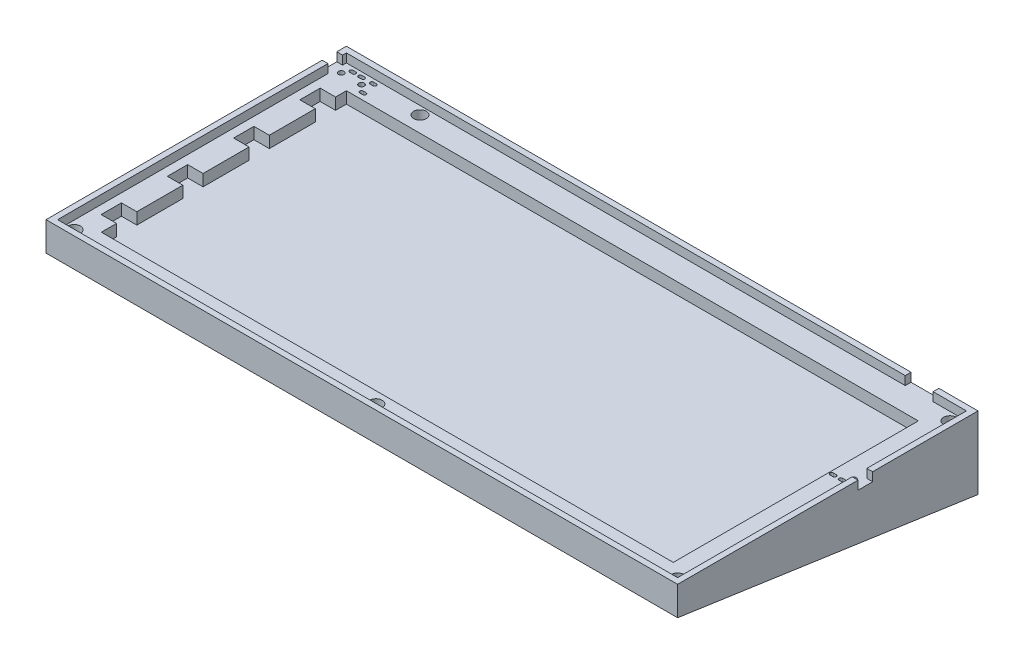
SolidWorks part; units mm, degrees
ref_plane "Front Plane" through (0, 0, 0) normal (0, 0, 1) x (1, 0, 0)
ref_plane "Top Plane" through (0, 0, 0) normal (0, 1, 0) x (1, 0, 0)
ref_plane "Right Plane" through (0, 0, 0) normal (1, 0, 0) x (0, 0, -1)
sketch "Sketch1" plane through (0, 0, 0) normal (0, 1, 0) x (1, 0, 0)
  line L0 (209.8674, 60.2591) -> (204.7265, 55.1181)
  line L1 (204.7265, 55.1181) -> (172.0853, 55.1181)
  line L2 (178.9434, 59.6901) -> (179.0084, 59.7551)
  line L3 (179.0084, 59.7551) -> (179.0084, 61.9761)
  line L4 (178.9434, 52.0701) -> (179.0084, 52.1351)
  line L5 (179.0084, 52.1351) -> (179.0084, 54.3561)
  line L6 (175.8954, 77.4448) -> (175.8954, 73.4061)
  line L7 (175.8954, 73.4061) -> (174.6253, 72.1361)
  line L8 (174.6253, 72.1361) -> (35.6058, 72.1361)
  line L9 (35.6058, 72.1361) -> (28.857, 65.3874)
  line L10 (10.5944, 97.7292) -> (19.873, 97.7292)
  line L11 (19.873, 97.7292) -> (23.749, 93.8532)
  line L12 (23.749, 93.8532) -> (29.4641, 93.8532)
  line L13 (29.4641, 93.8532) -> (32.8931, 97.2822)
  line L14 (32.8931, 97.2822) -> (187.3254, 97.2822)
  line L15 (187.3254, 97.2822) -> (197.3584, 87.2492)
  line L16 (6.5939, 97.7292) -> (8.189, 97.7292)
  line L17 (8.189, 97.7292) -> (9.271, 96.6472)
  line L18 (9.271, 96.6472) -> (20.066, 96.6472)
  line L19 (20.066, 96.6472) -> (23.495, 93.2182)
  line L20 (23.495, 93.2182) -> (29.8451, 93.2182)
  line L21 (29.8451, 93.2182) -> (33.4011, 96.7742)
  line L22 (33.4011, 96.7742) -> (186.5634, 96.7742)
  line L23 (186.5634, 96.7742) -> (192.1514, 91.1862)
  line L24 (3.4925, 97.7292) -> (6.9876, 94.2342)
  line L25 (6.9876, 94.2342) -> (11.938, 94.2342)
  line L26 (11.938, 94.2342) -> (13.843, 96.1392)
  line L27 (13.843, 96.1392) -> (19.685, 96.1392)
  line L28 (19.685, 96.1392) -> (23.241, 92.5832)
  line L29 (23.241, 92.5832) -> (30.2261, 92.5832)
  line L30 (30.2261, 92.5832) -> (33.9091, 96.2662)
  line L31 (33.9091, 96.2662) -> (183.7694, 96.2662)
  line L32 (183.7694, 96.2662) -> (191.8974, 88.1382)
  line L33 (191.8974, 88.1382) -> (194.1834, 88.1382)
  line L34 (197.3584, 87.2492) -> (186.4364, 87.2492)
  line L35 (186.4364, 87.2492) -> (183.7694, 84.5822)
  line L36 (183.7694, 84.5822) -> (172.8473, 84.5822)
  line L37 (172.8473, 84.5822) -> (169.5453, 81.2802)
  line L38 (169.5453, 81.2802) -> (169.5453, 77.4442)
  line L39 (190.5004, 83.4392) -> (192.6444, 81.2952)
  line L40 (192.6444, 81.2952) -> (192.6444, 74.4391)
  line L41 (190.6274, 85.9792) -> (191.6434, 85.9792)
  line L42 (191.6434, 85.9792) -> (193.2944, 84.3282)
  line L43 (193.2944, 84.3282) -> (193.2944, 74.4391)
  line L44 (185.1664, 83.3122) -> (174.1173, 83.3122)
  line L45 (174.1173, 83.3122) -> (170.8153, 80.0102)
  line L46 (170.8153, 80.0102) -> (170.8153, 77.4447)
  line L47 (185.1664, 80.5182) -> (172.8473, 80.5182)
  line L48 (172.8473, 80.5182) -> (172.0853, 79.7562)
  line L49 (172.0853, 79.7562) -> (172.0853, 77.4447)
  line L50 (116.0122, 32.6264) -> (122.1869, 32.6264)
  line L51 (122.1869, 32.6264) -> (123.6881, 31.1252)
  line L52 (123.6881, 31.1252) -> (131.1303, 31.1252)
  line L53 (182.2454, 41.1735) -> (182.2454, 42.2911)
  line L54 (182.2454, 42.2911) -> (174.4983, 50.0381)
  line L55 (174.4983, 50.0381) -> (16.0478, 50.0381)
  line L56 (16.0478, 50.0381) -> (8.537, 42.5273)
  line L57 (191.9944, 74.4391) -> (191.9944, 80.7421)
  line L58 (191.9944, 80.7421) -> (192.0244, 80.7722)
  line L59 (47.6911, 78.3592) -> (49.8501, 78.3465)
  line L60 (27.3711, 78.3592) -> (29.5301, 78.3465)
  line L61 (7.0511, 78.3592) -> (9.2101, 78.3465)
  line L62 (44.8911, 84.8362) -> (48.301, 88.2461)
  line L63 (48.301, 88.2461) -> (49.176, 88.2461)
  line L64 (65.2111, 84.8362) -> (68.6211, 88.2461)
  line L65 (68.6211, 88.2461) -> (69.4961, 88.2461)
  line L66 (85.5311, 84.8362) -> (88.9411, 88.2461)
  line L67 (88.9411, 88.2461) -> (89.8161, 88.2461)
  line L68 (105.8512, 84.8362) -> (109.2611, 88.2461)
  line L69 (109.2611, 88.2461) -> (110.1362, 88.2461)
  line L70 (126.1712, 84.8362) -> (129.5812, 88.2461)
  line L71 (129.5812, 88.2461) -> (130.4562, 88.2461)
  line L72 (146.4913, 84.8362) -> (149.9012, 88.2461)
  line L73 (149.9012, 88.2461) -> (150.7763, 88.2461)
  line L74 (68.0112, 78.3592) -> (70.1702, 78.3465)
  line L75 (88.3302, 78.3592) -> (90.4783, 78.3592)
  line L76 (90.4783, 78.3592) -> (90.4913, 78.3462)
  line L77 (128.9713, 78.3592) -> (131.1303, 78.3465)
  line L78 (149.2913, 78.3592) -> (151.4503, 78.3465)
  line L79 (24.572, 84.8362) -> (27.9807, 88.2474)
  line L80 (27.9807, 88.2474) -> (28.857, 88.2474)
  line L81 (173.3553, 86.8941) -> (173.3553, 91.3132)
  line L82 (173.3553, 91.3132) -> (172.4663, 92.2022)
  line L83 (172.4663, 92.2022) -> (154.7322, 92.2022)
  line L84 (154.7322, 92.2022) -> (150.7762, 88.2461)
  line L85 (174.6253, 86.8941) -> (174.6253, 90.8052)
  line L86 (174.6253, 90.8052) -> (172.7203, 92.7102)
  line L87 (172.7203, 92.7102) -> (134.9202, 92.7102)
  line L88 (134.9202, 92.7102) -> (130.4562, 88.2461)
  line L89 (110.1361, 88.2461) -> (115.1081, 93.2182)
  line L90 (115.1081, 93.2182) -> (172.9743, 93.2182)
  line L91 (172.9743, 93.2182) -> (175.8954, 90.2972)
  line L92 (175.8954, 90.2972) -> (175.8954, 86.8941)
  line L93 (28.856, 88.2461) -> (35.86, 95.2502)
  line L94 (35.86, 95.2502) -> (173.9903, 95.2502)
  line L95 (173.9903, 95.2502) -> (180.9754, 88.2652)
  line L96 (180.9754, 88.2652) -> (180.9754, 86.8941)
  line L97 (179.7054, 77.4448) -> (179.7054, 74.9301)
  line L98 (179.7054, 74.9301) -> (175.3874, 70.6121)
  line L99 (175.3874, 70.6121) -> (95.0419, 70.6121)
  line L100 (95.0419, 70.6121) -> (89.8171, 65.3874)
  line L101 (182.2454, 77.4448) -> (182.2454, 75.9462)
  line L102 (182.2454, 75.9462) -> (175.8954, 69.5961)
  line L103 (175.8954, 69.5961) -> (134.666, 69.5961)
  line L104 (134.666, 69.5961) -> (130.4572, 65.3874)
  line L105 (150.7772, 65.3874) -> (154.478, 69.0881)
  line L106 (154.478, 69.0881) -> (176.1494, 69.0881)
  line L107 (176.1494, 69.0881) -> (183.5154, 76.4542)
  line L108 (183.5154, 76.4542) -> (183.5154, 77.4448)
  line L109 (177.1654, 77.4448) -> (177.1654, 73.9141)
  line L110 (177.1654, 73.9141) -> (174.8793, 71.6281)
  line L111 (174.8793, 71.6281) -> (55.4178, 71.6281)
  line L112 (55.4178, 71.6281) -> (49.177, 65.3874)
  line L113 (180.9754, 77.4448) -> (180.9754, 75.4382)
  line L114 (180.9754, 75.4382) -> (175.6414, 70.1041)
  line L115 (175.6414, 70.1041) -> (114.8539, 70.1041)
  line L116 (114.8539, 70.1041) -> (110.1372, 65.3874)
  line L117 (178.4354, 77.4448) -> (178.4354, 74.4221)
  line L118 (178.4354, 74.4221) -> (175.1334, 71.1201)
  line L119 (175.1334, 71.1201) -> (75.2299, 71.1201)
  line L120 (75.2299, 71.1201) -> (69.4971, 65.3874)
  line L121 (4.251, 84.8362) -> (7.6609, 88.2461)
  line L122 (7.6609, 88.2461) -> (8.536, 88.2461)
  line L123 (4.251, 61.9761) -> (7.6609, 65.3861)
  line L124 (7.6609, 65.3861) -> (8.536, 65.3861)
  line L125 (24.571, 61.9761) -> (27.981, 65.3861)
  line L126 (27.981, 65.3861) -> (28.856, 65.3861)
  line L127 (44.8911, 61.9761) -> (48.301, 65.3861)
  line L128 (48.301, 65.3861) -> (49.176, 65.3861)
  line L129 (65.2111, 61.9761) -> (68.6211, 65.3861)
  line L130 (68.6211, 65.3861) -> (69.4961, 65.3861)
  line L131 (85.5311, 61.9761) -> (88.9411, 65.3861)
  line L132 (88.9411, 65.3861) -> (89.8161, 65.3861)
  line L133 (105.8514, 61.9761) -> (109.2614, 65.3861)
  line L134 (109.2614, 65.3861) -> (110.1362, 65.3861)
  line L135 (126.1712, 61.9761) -> (129.5812, 65.3861)
  line L136 (129.5812, 65.3861) -> (130.4562, 65.3861)
  line L137 (146.4913, 61.9761) -> (149.9012, 65.3861)
  line L138 (149.9012, 65.3861) -> (150.7763, 65.3861)
  line L139 (4.251, 39.1161) -> (7.6609, 42.526)
  line L140 (7.6609, 42.526) -> (8.536, 42.526)
  line L141 (24.571, 39.1161) -> (27.981, 42.526)
  line L142 (27.981, 42.526) -> (28.856, 42.526)
  line L143 (44.8911, 39.1161) -> (48.301, 42.526)
  line L144 (48.301, 42.526) -> (49.176, 42.526)
  line L145 (65.2111, 39.1161) -> (68.6211, 42.526)
  line L146 (68.6211, 42.526) -> (69.4961, 42.526)
  line L147 (85.5311, 39.1161) -> (88.9411, 42.526)
  line L148 (88.9411, 42.526) -> (89.8161, 42.526)
  line L149 (105.8514, 39.1161) -> (109.2614, 42.526)
  line L150 (109.2614, 42.526) -> (110.1362, 42.526)
  line L151 (126.1712, 39.1161) -> (129.5812, 42.526)
  line L152 (129.5812, 42.526) -> (130.4562, 42.526)
  line L153 (146.4913, 39.1161) -> (149.9012, 42.526)
  line L154 (149.9012, 42.526) -> (150.7763, 42.526)
  line L155 (4.251, 16.256) -> (7.6609, 19.666)
  line L156 (7.6609, 19.666) -> (8.536, 19.666)
  line L157 (24.571, 16.256) -> (27.981, 19.666)
  line L158 (27.981, 19.666) -> (28.856, 19.666)
  line L159 (44.8911, 16.256) -> (48.301, 19.666)
  line L160 (48.301, 19.666) -> (49.176, 19.666)
  line L161 (65.2111, 16.256) -> (68.6211, 19.666)
  line L162 (68.6211, 19.666) -> (69.4961, 19.666)
  line L163 (85.5311, 16.256) -> (88.9411, 19.666)
  line L164 (88.9411, 19.666) -> (89.8161, 19.666)
  line L165 (105.8514, 16.256) -> (109.2614, 19.666)
  line L166 (109.2614, 19.666) -> (110.1362, 19.666)
  line L167 (126.1712, 16.256) -> (129.5812, 19.666)
  line L168 (129.5812, 19.666) -> (130.4562, 19.666)
  line L169 (146.4913, 16.256) -> (149.9012, 19.666)
  line L170 (149.9012, 19.666) -> (150.7763, 19.666)
  line L171 (174.6253, 41.1735) -> (174.6253, 45.3391)
  line L172 (174.6253, 45.3391) -> (172.9743, 46.9901)
  line L173 (172.9743, 46.9901) -> (134.92, 46.9901)
  line L174 (134.92, 46.9901) -> (130.4572, 42.5273)
  line L175 (178.4354, 41.1735) -> (178.4354, 43.8151)
  line L176 (178.4354, 43.8151) -> (173.7363, 48.5141)
  line L177 (173.7363, 48.5141) -> (75.4839, 48.5141)
  line L178 (75.4839, 48.5141) -> (69.4971, 42.5273)
  line L179 (175.8954, 41.1735) -> (175.8954, 44.8311)
  line L180 (175.8954, 44.8311) -> (173.2283, 47.4981)
  line L181 (173.2283, 47.4981) -> (115.108, 47.4981)
  line L182 (115.108, 47.4981) -> (110.1372, 42.5273)
  line L183 (173.3553, 41.1735) -> (173.3553, 45.8471)
  line L184 (173.3553, 45.8471) -> (172.7203, 46.4821)
  line L185 (172.7203, 46.4821) -> (154.0513, 46.4821)
  line L186 (154.0513, 46.4821) -> (150.7772, 43.208)
  line L187 (150.7772, 43.208) -> (150.7772, 42.5273)
  line L188 (183.5154, 31.7247) -> (183.5154, 30.7341)
  line L189 (183.5154, 30.7341) -> (176.4034, 23.622)
  line L190 (176.4034, 23.622) -> (154.732, 23.622)
  line L191 (154.732, 23.622) -> (150.7772, 19.6673)
  line L192 (182.2454, 31.7247) -> (182.2454, 30.2261)
  line L193 (182.2454, 30.2261) -> (176.1494, 24.13)
  line L194 (176.1494, 24.13) -> (134.92, 24.13)
  line L195 (134.92, 24.13) -> (130.4572, 19.6673)
  line L196 (180.9754, 31.7247) -> (180.9754, 29.7181)
  line L197 (180.9754, 29.7181) -> (175.8954, 24.638)
  line L198 (175.8954, 24.638) -> (115.108, 24.638)
  line L199 (115.108, 24.638) -> (110.1372, 19.6673)
  line L200 (179.7054, 31.7247) -> (179.7054, 29.2101)
  line L201 (179.7054, 29.2101) -> (175.6414, 25.1461)
  line L202 (175.6414, 25.1461) -> (95.2959, 25.1461)
  line L203 (95.2959, 25.1461) -> (89.8171, 19.6673)
  line L204 (178.4354, 31.7247) -> (178.4354, 28.7021)
  line L205 (178.4354, 28.7021) -> (175.3874, 25.6541)
  line L206 (175.3874, 25.6541) -> (75.4839, 25.6541)
  line L207 (75.4839, 25.6541) -> (69.4971, 19.6673)
  line L208 (174.6253, 31.7247) -> (174.6253, 27.8131)
  line L209 (174.6253, 27.8131) -> (173.9903, 27.1781)
  line L210 (173.9903, 27.1781) -> (16.0478, 27.1781)
  line L211 (16.0478, 27.1781) -> (8.537, 19.6673)
  line L212 (7.0511, 55.4991) -> (9.2101, 55.4864)
  line L213 (27.3711, 55.4991) -> (29.5301, 55.4864)
  line L214 (47.6911, 55.4991) -> (49.8501, 55.4864)
  line L215 (68.0112, 55.4991) -> (70.1702, 55.4864)
  line L216 (88.3312, 55.4991) -> (90.4902, 55.4864)
  line L217 (108.6513, 55.4991) -> (110.8103, 55.4864)
  line L218 (128.9713, 55.4991) -> (131.1303, 55.4864)
  line L219 (149.2913, 55.4991) -> (151.4503, 55.4864)
  line L220 (7.0511, 32.6391) -> (9.2101, 32.6264)
  line L221 (47.6911, 32.6391) -> (49.8501, 32.6264)
  line L222 (68.0112, 32.6391) -> (70.1702, 32.6264)
  line L223 (88.3312, 32.6391) -> (90.4902, 32.6264)
  line L224 (108.6513, 32.6391) -> (110.8103, 32.6264)
  line L225 (128.9713, 32.6391) -> (131.1303, 32.6264)
  line L226 (149.2913, 32.6391) -> (151.4503, 32.6264)
  line L227 (7.0511, 9.779) -> (9.2101, 9.7663)
  line L228 (27.3711, 9.779) -> (29.5301, 9.7663)
  line L229 (47.6911, 9.779) -> (49.8501, 9.7663)
  line L230 (68.0112, 9.779) -> (70.1702, 9.7663)
  line L231 (88.3312, 9.779) -> (90.4902, 9.7663)
  line L232 (108.6513, 9.779) -> (110.8103, 9.7663)
  line L233 (128.9713, 9.779) -> (131.1303, 9.7663)
  line L234 (149.2913, 9.779) -> (151.4503, 9.7663)
  line L235 (14.412, 32.6264) -> (20.5867, 32.6264)
  line L236 (20.5867, 32.6264) -> (22.0879, 31.1252)
  line L237 (22.0879, 31.1252) -> (29.5301, 31.1252)
  line L238 (29.5311, 55.4862) -> (29.5311, 56.0854)
  line L239 (29.5311, 56.0854) -> (30.0876, 56.6419)
  line L240 (49.8512, 55.4862) -> (49.8512, 55.8568)
  line L241 (49.8512, 55.8568) -> (50.6362, 56.6419)
  line L242 (70.1712, 55.4862) -> (70.1712, 56.0739)
  line L243 (70.1712, 56.0739) -> (70.7391, 56.6419)
  line L244 (90.4912, 55.4862) -> (90.4912, 56.1362)
  line L245 (90.4912, 56.1362) -> (90.9969, 56.6419)
  line L246 (110.8113, 55.4862) -> (110.8113, 56.187)
  line L247 (110.8113, 56.187) -> (111.2661, 56.6419)
  line L248 (131.1313, 55.4862) -> (131.1313, 56.0739)
  line L249 (131.1313, 56.0739) -> (131.6993, 56.6419)
  line L250 (151.4514, 55.4862) -> (151.4514, 56.2378)
  line L251 (151.4514, 56.2378) -> (151.8554, 56.6419)
  line L252 (9.21, 78.3465) -> (9.21, 78.8062)
  line L253 (9.21, 78.8062) -> (9.906, 79.5022)
  line L254 (9.906, 79.5022) -> (164.3383, 79.5022)
  line L255 (151.4503, 78.3465) -> (151.4503, 78.9332)
  line L256 (151.4503, 78.9332) -> (152.0193, 79.5022)
  line L257 (131.1313, 78.3462) -> (131.1313, 78.9461)
  line L258 (131.1313, 78.9461) -> (131.6874, 79.5022)
  line L259 (110.8113, 78.3462) -> (110.8113, 78.9823)
  line L260 (110.8113, 78.9823) -> (111.3311, 79.5022)
  line L261 (90.4902, 78.3465) -> (90.4902, 78.9332)
  line L262 (90.4902, 78.9332) -> (91.0592, 79.5022)
  line L263 (70.1702, 78.3465) -> (70.1702, 79.0602)
  line L264 (70.1702, 79.0602) -> (70.6121, 79.5022)
  line L265 (49.8512, 78.3462) -> (49.8512, 78.9046)
  line L266 (49.8512, 78.9046) -> (50.4487, 79.5022)
  line L267 (29.5311, 78.3462) -> (29.5311, 78.9681)
  line L268 (29.5311, 78.9681) -> (30.0652, 79.5022)
  line L269 (156.6523, 78.3465) -> (159.2583, 78.3592)
  line L270 (6.096, 53.9751) -> (9.2101, 53.9853)
  line L271 (9.2111, 55.4862) -> (9.2111, 55.9459)
  line L272 (9.2111, 55.9459) -> (9.9071, 56.6419)
  line L273 (9.9071, 56.6419) -> (164.3394, 56.6419)
  line L274 (27.3711, 32.6391) -> (29.5301, 32.6264)
  line L275 (29.5311, 32.6261) -> (29.5311, 33.1399)
  line L276 (29.5311, 33.1399) -> (30.186, 33.7948)
  line L277 (49.8512, 32.6261) -> (49.8512, 33.1762)
  line L278 (49.8512, 33.1762) -> (50.4697, 33.7948)
  line L279 (70.1712, 32.6261) -> (70.1712, 33.1943)
  line L280 (70.1712, 33.1943) -> (70.7716, 33.7948)
  line L281 (90.4912, 32.6261) -> (90.4912, 33.3032)
  line L282 (90.4912, 33.3032) -> (90.9828, 33.7948)
  line L283 (110.8113, 32.6261) -> (110.8113, 33.2125)
  line L284 (110.8113, 33.2125) -> (111.3936, 33.7948)
  line L285 (131.1313, 32.6261) -> (131.1313, 33.1762)
  line L286 (131.1313, 33.1762) -> (131.7499, 33.7948)
  line L287 (151.4514, 32.6261) -> (151.4514, 33.1943)
  line L288 (151.4514, 33.1943) -> (152.0518, 33.7948)
  line L289 (9.144, 32.6391) -> (9.144, 33.0988)
  line L290 (9.144, 33.0988) -> (9.8273, 33.7821)
  line L291 (9.8273, 33.7821) -> (164.3383, 33.7821)
  line L292 (9.2111, 9.7661) -> (9.2111, 10.2258)
  line L293 (9.2111, 10.2258) -> (9.9073, 10.922)
  line L294 (9.9073, 10.922) -> (164.3383, 10.922)
  line L295 (29.5311, 9.7661) -> (29.5311, 10.4171)
  line L296 (29.5311, 10.4171) -> (30.0358, 10.9218)
  line L297 (49.8512, 9.7661) -> (49.8512, 10.2719)
  line L298 (49.8512, 10.2719) -> (50.501, 10.9218)
  line L299 (70.1712, 9.7661) -> (70.1712, 10.3445)
  line L300 (70.1712, 10.3445) -> (70.7485, 10.9218)
  line L301 (90.4912, 9.7661) -> (90.4912, 10.4352)
  line L302 (90.4912, 10.4352) -> (90.9778, 10.9218)
  line L303 (110.8113, 9.7661) -> (110.8113, 10.4715)
  line L304 (110.8113, 10.4715) -> (111.2615, 10.9218)
  line L305 (131.1313, 9.7661) -> (131.1313, 10.4808)
  line L306 (131.1313, 10.4808) -> (131.5723, 10.9218)
  line L307 (151.4514, 9.7661) -> (151.4514, 10.3538)
  line L308 (151.4514, 10.3538) -> (152.0193, 10.9218)
  line L309 (177.1654, 41.1735) -> (177.1654, 44.3231)
  line L310 (177.1654, 44.3231) -> (173.4823, 48.0061)
  line L311 (173.4823, 48.0061) -> (95.2959, 48.0061)
  line L312 (95.2959, 48.0061) -> (89.8171, 42.5273)
  line L313 (6.096, 31.1151) -> (9.2101, 31.1252)
  line L314 (156.6523, 55.4864) -> (159.2583, 55.4991)
  line L315 (6.096, 8.255) -> (9.2101, 8.2652)
  line L316 (159.2583, 32.6391) -> (156.6523, 32.6264)
  line L317 (170.8153, 34.7981) -> (170.8153, 31.7242)
  line L318 (172.0853, 34.7981) -> (172.0853, 31.7242)
  line L319 (170.8153, 77.4442) -> (170.8153, 73.6601)
  line L320 (172.0853, 77.4442) -> (172.0853, 73.6601)
  line L321 (169.5453, 31.7242) -> (169.4834, 31.6622)
  line L322 (169.4834, 31.6622) -> (169.4834, 29.4641)
  line L323 (169.4834, 29.4641) -> (172.8473, 29.4641)
  line L324 (172.8473, 29.4641) -> (173.3553, 29.9721)
  line L325 (173.3553, 29.9721) -> (173.3553, 31.7242)
  line L326 (174.6253, 77.4448) -> (174.6253, 73.2791)
  line L327 (174.6253, 73.2791) -> (173.9903, 72.6441)
  line L328 (173.9903, 72.6441) -> (15.7938, 72.6441)
  line L329 (15.7938, 72.6441) -> (8.537, 65.3874)
  line L330 (189.5494, 74.4221) -> (189.5664, 74.4391)
  line L331 (189.5664, 74.4391) -> (191.3445, 74.4391)
  line L332 (189.5494, 68.4531) -> (189.6594, 68.5631)
  line L333 (189.6594, 68.5631) -> (191.3445, 68.5631)
  line L334 (156.6523, 9.7663) -> (159.5123, 9.779)
  line L335 (169.5453, 34.7981) -> (169.5453, 31.7241)
  line L336 (169.5453, 77.4442) -> (169.5453, 73.6601)
  line L337 (189.3574, 75.9462) -> (189.5494, 75.7541)
  line L338 (189.5494, 75.7541) -> (189.5494, 74.4221)
  line L339 (14.412, 9.7663) -> (20.5867, 9.7663)
  line L340 (20.5867, 9.7663) -> (22.0879, 8.2652)
  line L341 (22.0879, 8.2652) -> (29.5301, 8.2652)
  line L342 (34.732, 9.7663) -> (40.9068, 9.7663)
  line L343 (40.9068, 9.7663) -> (42.4079, 8.2652)
  line L344 (42.4079, 8.2652) -> (49.8501, 8.2652)
  line L345 (55.0521, 9.7663) -> (61.2268, 9.7663)
  line L346 (61.2268, 9.7663) -> (62.728, 8.2652)
  line L347 (62.728, 8.2652) -> (70.1702, 8.2652)
  line L348 (75.3721, 9.7663) -> (81.5469, 9.7663)
  line L349 (81.5469, 9.7663) -> (83.048, 8.2652)
  line L350 (83.048, 8.2652) -> (90.4902, 8.2652)
  line L351 (95.6922, 9.7663) -> (101.8669, 9.7663)
  line L352 (101.8669, 9.7663) -> (103.368, 8.2652)
  line L353 (103.368, 8.2652) -> (110.8103, 8.2652)
  line L354 (116.0122, 9.7663) -> (122.1869, 9.7663)
  line L355 (122.1869, 9.7663) -> (123.6881, 8.2652)
  line L356 (123.6881, 8.2652) -> (131.1303, 8.2652)
  line L357 (136.3322, 9.7663) -> (142.507, 9.7663)
  line L358 (142.507, 9.7663) -> (144.0081, 8.2652)
  line L359 (144.0081, 8.2652) -> (151.4503, 8.2652)
  line L360 (136.3322, 32.6264) -> (143.777, 32.6264)
  line L361 (143.777, 32.6264) -> (145.2781, 31.1252)
  line L362 (145.2781, 31.1252) -> (151.4503, 31.1252)
  line L363 (95.6922, 32.6264) -> (101.8669, 32.6264)
  line L364 (101.8669, 32.6264) -> (103.368, 31.1252)
  line L365 (103.368, 31.1252) -> (110.8103, 31.1252)
  line L366 (75.3721, 32.6264) -> (81.5469, 32.6264)
  line L367 (81.5469, 32.6264) -> (83.048, 31.1252)
  line L368 (83.048, 31.1252) -> (90.4902, 31.1252)
  line L369 (55.0521, 32.6264) -> (61.2268, 32.6264)
  line L370 (61.2268, 32.6264) -> (62.728, 31.1252)
  line L371 (62.728, 31.1252) -> (70.1702, 31.1252)
  line L372 (34.732, 32.6264) -> (40.9068, 32.6264)
  line L373 (40.9068, 32.6264) -> (42.4079, 31.1252)
  line L374 (42.4079, 31.1252) -> (49.8501, 31.1252)
  line L375 (14.412, 55.4864) -> (20.5867, 55.4864)
  line L376 (20.5867, 55.4864) -> (22.0879, 53.9853)
  line L377 (22.0879, 53.9853) -> (29.5301, 53.9853)
  line L378 (34.732, 55.4864) -> (40.9068, 55.4864)
  line L379 (40.9068, 55.4864) -> (42.4079, 53.9853)
  line L380 (42.4079, 53.9853) -> (49.8501, 53.9853)
  line L381 (55.0521, 55.4864) -> (61.2268, 55.4864)
  line L382 (61.2268, 55.4864) -> (62.728, 53.9853)
  line L383 (62.728, 53.9853) -> (70.1702, 53.9853)
  line L384 (75.3721, 55.4864) -> (81.5469, 55.4864)
  line L385 (81.5469, 55.4864) -> (83.048, 53.9853)
  line L386 (83.048, 53.9853) -> (90.4902, 53.9853)
  line L387 (95.6922, 55.4864) -> (101.8669, 55.4864)
  line L388 (101.8669, 55.4864) -> (103.368, 53.9853)
  line L389 (103.368, 53.9853) -> (110.8103, 53.9853)
  line L390 (116.0122, 55.4864) -> (122.1869, 55.4864)
  line L391 (122.1869, 55.4864) -> (123.6881, 53.9853)
  line L392 (123.6881, 53.9853) -> (131.1303, 53.9853)
  line L393 (136.3322, 55.4864) -> (142.507, 55.4864)
  line L394 (142.507, 55.4864) -> (144.0081, 53.9853)
  line L395 (144.0081, 53.9853) -> (151.4503, 53.9853)
  line L396 (136.3322, 78.3465) -> (142.507, 78.3465)
  line L397 (142.507, 78.3465) -> (144.0081, 76.8453)
  line L398 (144.0081, 76.8453) -> (151.4503, 76.8453)
  line L399 (116.0122, 78.3465) -> (122.1869, 78.3465)
  line L400 (122.1869, 78.3465) -> (123.6881, 76.8453)
  line L401 (123.6881, 76.8453) -> (131.1303, 76.8453)
  line L402 (95.6922, 78.3465) -> (101.8669, 78.3465)
  line L403 (101.8669, 78.3465) -> (103.368, 76.8453)
  line L404 (103.368, 76.8453) -> (110.8103, 76.8453)
  line L405 (75.3721, 78.3465) -> (81.5469, 78.3465)
  line L406 (81.5469, 78.3465) -> (83.048, 76.8453)
  line L407 (83.048, 76.8453) -> (90.4902, 76.8453)
  line L408 (55.0521, 78.3465) -> (61.2268, 78.3465)
  line L409 (61.2268, 78.3465) -> (62.728, 76.8453)
  line L410 (62.728, 76.8453) -> (70.1702, 76.8453)
  line L411 (34.732, 78.3465) -> (40.9068, 78.3465)
  line L412 (40.9068, 78.3465) -> (42.4079, 76.8453)
  line L413 (42.4079, 76.8453) -> (49.8501, 76.8453)
  line L414 (14.412, 78.3465) -> (20.5867, 78.3465)
  line L415 (20.5867, 78.3465) -> (22.0879, 76.8453)
  line L416 (22.0879, 76.8453) -> (29.5301, 76.8453)
  line L417 (191.3437, 68.5624) -> (191.3437, 70.8204)
  line L418 (191.3437, 70.8204) -> (191.8974, 71.3741)
  line L419 (191.8974, 71.3741) -> (194.4374, 71.3741)
  line L420 (194.4374, 71.3741) -> (195.2451, 70.5664)
  line L421 (195.2451, 70.5664) -> (195.2451, 68.5624)
  line L422 (192.0244, 70.1041) -> (191.9944, 70.0741)
  line L423 (191.9944, 70.0741) -> (191.9944, 68.5631)
  line L424 (108.6513, 78.3592) -> (110.8103, 78.3465)
  line L425 (179.0093, 67.4371) -> (188.5334, 67.4371)
  line L426 (188.5334, 67.4371) -> (189.5494, 68.4531)
  line L427 (179.0084, 67.4371) -> (178.9434, 67.3721)
  line L428 (178.9434, 67.3721) -> (178.9434, 65.1511)
  line L429 (193.2944, 68.5624) -> (193.2944, 67.1831)
  line L430 (193.2944, 67.1831) -> (192.2784, 66.1671)
  line L431 (192.2784, 66.1671) -> (185.0394, 66.1671)
  line L432 (185.0394, 66.1671) -> (184.0234, 65.1511)
  line L433 (192.6441, 68.5624) -> (192.6441, 67.2949)
  line L434 (192.6441, 67.2949) -> (192.1514, 66.8021)
  line L435 (192.1514, 66.8021) -> (183.1344, 66.8021)
  line L436 (183.1344, 66.8021) -> (181.4834, 65.1511)
  line L437 (180.9754, 41.1735) -> (180.9754, 42.7991)
  line L438 (180.9754, 42.7991) -> (174.2443, 49.5301)
  line L439 (174.2443, 49.5301) -> (35.8598, 49.5301)
  line L440 (35.8598, 49.5301) -> (28.857, 42.5273)
  line L441 (49.176, 88.2461) -> (55.672, 94.7422)
  line L442 (55.672, 94.7422) -> (173.7363, 94.7422)
  line L443 (173.7363, 94.7422) -> (179.7054, 88.7732)
  line L444 (179.7054, 88.7732) -> (179.7054, 86.8941)
  line L445 (177.1654, 31.7247) -> (177.1654, 28.1941)
  line L446 (177.1654, 28.1941) -> (175.1334, 26.1621)
  line L447 (175.1334, 26.1621) -> (55.6718, 26.1621)
  line L448 (55.6718, 26.1621) -> (49.177, 19.6673)
  line L449 (69.4961, 88.2461) -> (75.484, 94.2342)
  line L450 (75.484, 94.2342) -> (173.4823, 94.2342)
  line L451 (173.4823, 94.2342) -> (178.4354, 89.2812)
  line L452 (178.4354, 89.2812) -> (178.4354, 86.8941)
  line L453 (210.8204, 92.9642) -> (210.8204, 72.5171)
  line L454 (210.8204, 72.5171) -> (206.8664, 68.5631)
  line L455 (206.8664, 68.5631) -> (195.2443, 68.5631)
  line L456 (206.7673, 60.2591) -> (202.6424, 56.1341)
  line L457 (202.6424, 56.1341) -> (170.8153, 56.1341)
  line L458 (89.8161, 88.2461) -> (95.2961, 93.7262)
  line L459 (95.2961, 93.7262) -> (173.2283, 93.7262)
  line L460 (173.2283, 93.7262) -> (177.1654, 89.7892)
  line L461 (177.1654, 89.7892) -> (177.1654, 86.8941)
  line L462 (182.2454, 86.8936) -> (182.2454, 87.7572)
  line L463 (182.2454, 87.7572) -> (174.2443, 95.7582)
  line L464 (174.2443, 95.7582) -> (34.2901, 95.7582)
  line L465 (34.2901, 95.7582) -> (29.8451, 91.3132)
  line L466 (29.8451, 91.3132) -> (11.6027, 91.3132)
  line L467 (11.6027, 91.3132) -> (8.537, 88.2474)
  line L468 (179.7054, 41.1735) -> (179.7054, 43.3071)
  line L469 (179.7054, 43.3071) -> (173.9903, 49.0221)
  line L470 (173.9903, 49.0221) -> (55.6718, 49.0221)
  line L471 (55.6718, 49.0221) -> (49.177, 42.5273)
  line L472 (175.8954, 31.7247) -> (175.8954, 27.6861)
  line L473 (175.8954, 27.6861) -> (174.8793, 26.6701)
  line L474 (174.8793, 26.6701) -> (35.8598, 26.6701)
  line L475 (35.8598, 26.6701) -> (28.857, 19.6673)
  line L476 (0, 99.0602) -> (213.3604, 99.0602)
  line L477 (213.3604, 99.0602) -> (213.3604, 0)
  line L478 (213.3604, 0) -> (0, 0)
  line L479 (0, 0) -> (0, 99.0602)
  line L480 (184.0234, 59.6901) -> (184.0234, 52.0701)
  line L481 (184.0234, 65.1511) -> (184.0234, 59.6901)
  line L482 (181.4834, 59.6901) -> (181.4834, 52.0701)
  line L483 (181.4834, 65.1511) -> (181.4834, 59.6901)
  line L484 (178.9434, 59.6901) -> (178.9434, 52.0701)
  line L485 (178.9434, 65.1511) -> (178.9434, 59.6901)
  line L486 (188.2144, 85.9792) -> (187.0714, 85.9792)
  line L487 (187.0714, 85.9792) -> (185.1664, 84.0742)
  line L488 (185.1664, 84.0742) -> (185.1664, 83.3122)
  line L489 (188.2144, 83.4392) -> (187.1984, 83.4392)
  line L490 (187.1984, 83.4392) -> (185.1664, 81.4072)
  line L491 (185.1664, 81.4072) -> (185.1664, 80.5182)
  line L492 (206.8834, 96.1392) -> (207.6454, 96.1392)
  line L493 (207.6454, 96.1392) -> (210.8204, 92.9642)
  line L494 (188.2144, 88.5192) -> (190.5004, 88.5192)
  line L495 (190.5004, 88.5192) -> (192.0244, 86.9952)
  line L496 (192.0244, 86.9952) -> (192.0244, 80.7722)
  line L497 (6.096, 31.1151) -> (3.048, 31.1151)
  line L498 (3.048, 31.1151) -> (1.016, 33.1471)
  line L499 (1.016, 33.1471) -> (1.016, 46.4821)
  line L500 (1.016, 46.4821) -> (2.921, 48.3871)
  line L501 (2.921, 48.3871) -> (155.8293, 48.3871)
  line L502 (155.8293, 48.3871) -> (159.2583, 51.8161)
  line L503 (159.2583, 51.8161) -> (159.2583, 55.4991)
  line L504 (188.2144, 85.9792) -> (190.6274, 85.9792)
  line L505 (146.1773, 78.3592) -> (146.1773, 75.6922)
  line L506 (146.1773, 75.6922) -> (147.8283, 74.0411)
  line L507 (105.5372, 78.3592) -> (105.5372, 75.6922)
  line L508 (105.5372, 75.6922) -> (107.1882, 74.0411)
  line L509 (85.2172, 78.3592) -> (85.2172, 75.6922)
  line L510 (85.2172, 75.6922) -> (86.8682, 74.0411)
  line L511 (64.8971, 78.3592) -> (64.8971, 75.6922)
  line L512 (64.8971, 75.6922) -> (66.5481, 74.0411)
  line L513 (44.4501, 78.3592) -> (44.4501, 75.6922)
  line L514 (44.4501, 75.6922) -> (46.1011, 74.0411)
  line L515 (24.257, 78.3592) -> (24.257, 75.6922)
  line L516 (24.257, 75.6922) -> (25.9081, 74.0411)
  line L517 (24.257, 55.4991) -> (24.257, 52.8321)
  line L518 (24.257, 52.8321) -> (25.9081, 51.1811)
  line L519 (44.3231, 55.4991) -> (44.3231, 52.8321)
  line L520 (44.3231, 52.8321) -> (45.9741, 51.1811)
  line L521 (64.7701, 55.4991) -> (64.7701, 52.8321)
  line L522 (64.7701, 52.8321) -> (66.4211, 51.1811)
  line L523 (84.9632, 55.4991) -> (84.9632, 52.8321)
  line L524 (84.9632, 52.8321) -> (86.6142, 51.1811)
  line L525 (105.4102, 55.4991) -> (105.4102, 52.8321)
  line L526 (105.4102, 52.8321) -> (107.0612, 51.1811)
  line L527 (125.7303, 55.4991) -> (125.7303, 52.8321)
  line L528 (125.7303, 52.8321) -> (127.3813, 51.1811)
  line L529 (145.9233, 55.4991) -> (145.9233, 52.8321)
  line L530 (145.9233, 52.8321) -> (147.5743, 51.1811)
  line L531 (24.003, 32.6391) -> (24.003, 29.9721)
  line L532 (24.003, 29.9721) -> (25.6541, 28.3211)
  line L533 (44.3231, 32.6391) -> (44.3231, 29.9721)
  line L534 (44.3231, 29.9721) -> (45.9741, 28.3211)
  line L535 (64.7701, 32.6391) -> (64.7701, 29.9721)
  line L536 (64.7701, 29.9721) -> (66.4211, 28.3211)
  line L537 (84.9632, 32.6391) -> (84.9632, 29.9721)
  line L538 (84.9632, 29.9721) -> (86.6142, 28.3211)
  line L539 (105.4102, 32.6391) -> (105.4102, 29.9721)
  line L540 (105.4102, 29.9721) -> (107.0612, 28.3211)
  line L541 (125.7303, 32.6391) -> (125.7303, 29.9721)
  line L542 (125.7303, 29.9721) -> (127.3813, 28.3211)
  line L543 (146.0503, 32.6391) -> (146.0503, 29.9721)
  line L544 (146.0503, 29.9721) -> (147.7013, 28.3211)
  line L545 (24.13, 9.779) -> (24.13, 7.112)
  line L546 (24.13, 7.112) -> (25.7811, 5.461)
  line L547 (44.3231, 9.779) -> (44.3231, 7.112)
  line L548 (44.3231, 7.112) -> (45.9741, 5.461)
  line L549 (64.6431, 9.779) -> (64.6431, 7.112)
  line L550 (64.6431, 7.112) -> (66.2941, 5.461)
  line L551 (84.9632, 9.779) -> (84.9632, 7.112)
  line L552 (84.9632, 7.112) -> (86.6142, 5.461)
  line L553 (105.2832, 9.779) -> (105.2832, 7.112)
  line L554 (105.2832, 7.112) -> (106.9342, 5.461)
  line L555 (125.6033, 9.779) -> (125.6033, 7.112)
  line L556 (125.6033, 7.112) -> (127.2543, 5.461)
  line L557 (146.0503, 9.779) -> (146.0503, 7.112)
  line L558 (146.0503, 7.112) -> (147.7013, 5.461)
  line L559 (164.3394, 56.6419) -> (164.3394, 33.7832)
  line L560 (164.3394, 33.7832) -> (164.3383, 33.7821)
  line L561 (164.3383, 33.7821) -> (164.3383, 10.922)
  line L562 (6.096, 53.9751) -> (3.048, 53.9751)
  line L563 (3.048, 53.9751) -> (1.016, 56.0071)
  line L564 (1.016, 56.0071) -> (1.016, 69.3421)
  line L565 (1.016, 69.3421) -> (2.921, 71.2471)
  line L566 (2.921, 71.2471) -> (155.8293, 71.2471)
  line L567 (155.8293, 71.2471) -> (159.2583, 74.6761)
  line L568 (159.2583, 74.6761) -> (159.2583, 78.3592)
  line L569 (6.096, 8.255) -> (2.921, 8.255)
  line L570 (2.921, 8.255) -> (1.016, 10.16)
  line L571 (1.016, 10.16) -> (1.016, 23.495)
  line L572 (1.016, 23.495) -> (2.921, 25.4001)
  line L573 (2.921, 25.4001) -> (155.8293, 25.4001)
  line L574 (155.8293, 25.4001) -> (159.2583, 28.8291)
  line L575 (159.2583, 28.8291) -> (159.2583, 32.6391)
  line L576 (125.7303, 78.3592) -> (125.7303, 75.6922)
  line L577 (125.7303, 75.6922) -> (127.3813, 74.0411)
  line L578 (188.2144, 83.4392) -> (190.5004, 83.4392)
  line L579 (206.8834, 91.0592) -> (201.1684, 91.0592)
  line L580 (201.1684, 91.0592) -> (197.3584, 87.2492)
  line L581 (172.0853, 59.4373) -> (172.0853, 35.0521)
  line L582 (172.0853, 73.6601) -> (172.0853, 59.4373)
  line L583 (170.8153, 56.5925) -> (170.8153, 34.7981)
  line L584 (170.8153, 73.6601) -> (170.8153, 56.5925)
  line L585 (169.5453, 34.7981) -> (169.5453, 73.6601)
  line L586 (192.0244, 70.1041) -> (188.2144, 70.1041)
  line L587 (188.2144, 70.1041) -> (186.8174, 68.7071)
  line L588 (186.8174, 16.51) -> (180.0864, 9.779)
  line L589 (180.0864, 9.779) -> (159.5123, 9.779)
  line L590 (186.8174, 68.7071) -> (186.8174, 16.51)
  line L591 (164.3383, 79.5022) -> (164.3383, 83.9472)
  line L592 (164.3383, 83.9472) -> (178.5624, 98.1712)
  line L593 (178.5624, 98.1712) -> (204.8514, 98.1712)
  line L594 (204.8514, 98.1712) -> (206.8834, 96.1392)
  line L595 (169.5453, 73.6601) -> (169.5453, 74.8031)
  line L596 (169.5453, 74.8031) -> (170.6883, 75.9462)
  line L597 (170.6883, 75.9462) -> (189.3574, 75.9462)
  line L598 (194.1834, 88.1382) -> (201.4224, 80.8992)
  line L599 (201.4224, 80.8992) -> (206.8834, 80.8992)
  line L600 (202.7661, 60.2591) -> (199.0094, 64.0157)
  line L601 (199.0094, 64.0157) -> (199.0094, 72.6441)
  line L602 (199.0094, 72.6441) -> (201.5494, 75.1842)
  line L603 (201.5494, 75.1842) -> (206.3754, 75.1842)
  line L604 (206.3754, 75.1842) -> (209.9314, 78.7402)
  line L605 (209.9314, 78.7402) -> (209.9314, 88.7732)
  line L606 (209.9314, 88.7732) -> (207.6454, 91.0592)
  line L607 (207.6454, 91.0592) -> (206.8834, 91.0592)
  line L608 (164.3383, 79.5022) -> (164.3383, 56.6421)
  line L609 (192.1514, 91.1862) -> (192.9134, 90.4242)
  line L610 (192.9134, 90.4242) -> (192.9134, 80.1372)
  line L611 (192.9134, 80.1372) -> (192.0244, 79.2482)
  line L612 (192.0244, 79.2482) -> (188.7224, 79.2482)
  line L613 (188.7224, 79.2482) -> (188.2144, 79.7562)
  line L614 (188.2144, 79.7562) -> (188.2144, 80.8992)
  line L615 (179.6984, 61.5764) -> (179.6984, 62.3764)
  line L616 (178.5886, 61.2665) -> (179.3886, 61.2665)
  line L617 (178.5886, 62.6862) -> (179.3886, 62.6862)
  line L618 (178.0127, 61.2607) -> (177.2127, 61.2607)
  line L619 (176.9029, 61.5705) -> (176.9029, 62.3705)
  line L620 (178.0127, 62.6803) -> (177.2127, 62.6803)
  line L621 (179.6984, 53.9563) -> (179.6984, 54.7564)
  line L622 (178.5886, 53.6465) -> (179.3886, 53.6465)
  line L623 (178.5886, 55.0661) -> (179.3886, 55.0661)
  line L624 (178.0127, 53.6407) -> (177.2127, 53.6407)
  line L625 (176.9029, 53.9505) -> (176.9029, 54.7505)
  line L626 (178.0127, 55.0603) -> (177.2127, 55.0603)
  line L627 (185.2934, 60.9601) -> (185.2934, 58.4201)
  line L628 (185.2934, 58.4201) -> (175.1334, 58.4201)
  line L629 (175.1334, 58.4201) -> (175.1334, 60.9601)
  line L630 (175.1334, 60.9601) -> (177.0384, 60.9601)
  line L631 (185.2934, 60.9601) -> (177.0384, 60.9601)
  line L632 (185.2934, 53.3401) -> (185.2934, 50.8001)
  line L633 (185.2934, 50.8001) -> (175.1334, 50.8001)
  line L634 (175.1334, 50.8001) -> (175.1334, 53.3401)
  line L635 (175.1334, 53.3401) -> (177.0384, 53.3401)
  line L636 (185.2934, 53.3401) -> (177.0384, 53.3401)
  line L637 (0.193, 92.9871) -> (-1.778, 92.9871)
  line L638 (-1.778, 92.9871) -> (-1.778, 98.0442)
  line L639 (-1.778, 98.0442) -> (0.193, 98.0442)
  line L640 (12.193, 98.5042) -> (12.193, 94.1088)
  line L641 (0.193, 98.5042) -> (12.193, 98.5042)
  line L642 (0.193, 92.5042) -> (12.193, 92.5042)
  line L643 (0.193, 92.5042) -> (0.193, 98.5042)
  line L644 (213.1674, 65.0012) -> (215.1384, 65.0012)
  line L645 (215.1384, 65.0012) -> (215.1384, 59.9441)
  line L646 (215.1384, 59.9441) -> (213.1674, 59.9441)
  line L647 (201.1674, 59.4841) -> (201.1674, 63.8795)
  line L648 (213.1674, 59.4841) -> (201.1674, 59.4841)
  line L649 (213.1674, 65.4841) -> (201.1674, 65.4841)
  line L650 (213.1674, 65.4841) -> (213.1674, 59.4841)
  line L651 (185.2934, 66.4211) -> (185.2934, 63.8811)
  line L652 (185.2934, 63.8811) -> (175.1334, 63.8811)
  line L653 (175.1334, 63.8811) -> (175.1334, 66.4211)
  line L654 (175.1334, 66.4211) -> (177.0384, 66.4211)
  line L655 (185.2934, 66.4211) -> (177.0384, 66.4211)
  line L656 (2.286, 91.8212) -> (21.336, 91.8212)
  line L657 (21.336, 91.8212) -> (21.336, 72.7711)
  line L658 (21.336, 72.7711) -> (2.286, 72.7711)
  line L659 (2.286, 72.7711) -> (2.286, 91.8212)
  line L660 (15.811, 89.2962) -> (18.811, 89.2962)
  line L661 (18.811, 89.2962) -> (18.811, 86.2962)
  line L662 (18.811, 78.2962) -> (18.811, 75.2961)
  line L663 (18.811, 75.2961) -> (15.811, 75.2961)
  line L664 (7.811, 75.2961) -> (4.811, 75.2961)
  line L665 (4.811, 75.2961) -> (4.811, 78.2962)
  line L666 (4.811, 86.2962) -> (4.811, 89.2962)
  line L667 (4.811, 89.2962) -> (7.811, 89.2962)
  line L668 (22.6061, 91.8212) -> (41.6562, 91.8212)
  line L669 (41.6562, 91.8212) -> (41.6562, 72.7711)
  line L670 (41.6562, 72.7711) -> (22.6061, 72.7711)
  line L671 (22.6061, 72.7711) -> (22.6061, 91.8212)
  line L672 (36.1311, 89.2962) -> (39.1312, 89.2962)
  line L673 (39.1312, 89.2962) -> (39.1312, 86.2962)
  line L674 (39.1312, 78.2962) -> (39.1312, 75.2961)
  line L675 (39.1312, 75.2961) -> (36.1311, 75.2961)
  line L676 (28.1311, 75.2961) -> (25.1311, 75.2961)
  line L677 (25.1311, 75.2961) -> (25.1311, 78.2962)
  line L678 (25.1311, 86.2962) -> (25.1311, 89.2962)
  line L679 (25.1311, 89.2962) -> (28.1311, 89.2962)
  line L680 (42.9261, 91.8212) -> (61.9762, 91.8212)
  line L681 (61.9762, 91.8212) -> (61.9762, 72.7711)
  line L682 (61.9762, 72.7711) -> (42.9261, 72.7711)
  line L683 (42.9261, 72.7711) -> (42.9261, 91.8212)
  line L684 (56.4512, 89.2962) -> (59.4512, 89.2962)
  line L685 (59.4512, 89.2962) -> (59.4512, 86.2962)
  line L686 (59.4512, 78.2962) -> (59.4512, 75.2961)
  line L687 (59.4512, 75.2961) -> (56.4512, 75.2961)
  line L688 (48.4512, 75.2961) -> (45.4511, 75.2961)
  line L689 (45.4511, 75.2961) -> (45.4511, 78.2962)
  line L690 (45.4511, 86.2962) -> (45.4511, 89.2962)
  line L691 (45.4511, 89.2962) -> (48.4512, 89.2962)
  line L692 (63.2462, 91.8212) -> (82.2962, 91.8212)
  line L693 (82.2962, 91.8212) -> (82.2962, 72.7711)
  line L694 (82.2962, 72.7711) -> (63.2462, 72.7711)
  line L695 (63.2462, 72.7711) -> (63.2462, 91.8212)
  line L696 (76.7712, 89.2962) -> (79.7712, 89.2962)
  line L697 (79.7712, 89.2962) -> (79.7712, 86.2962)
  line L698 (79.7712, 78.2962) -> (79.7712, 75.2961)
  line L699 (79.7712, 75.2961) -> (76.7712, 75.2961)
  line L700 (68.7712, 75.2961) -> (65.7712, 75.2961)
  line L701 (65.7712, 75.2961) -> (65.7712, 78.2962)
  line L702 (65.7712, 86.2962) -> (65.7712, 89.2962)
  line L703 (65.7712, 89.2962) -> (68.7712, 89.2962)
  line L704 (83.5662, 91.8212) -> (102.6162, 91.8212)
  line L705 (102.6162, 91.8212) -> (102.6162, 72.7711)
  line L706 (102.6162, 72.7711) -> (83.5662, 72.7711)
  line L707 (83.5662, 72.7711) -> (83.5662, 91.8212)
  line L708 (97.0912, 89.2962) -> (100.0912, 89.2962)
  line L709 (100.0912, 89.2962) -> (100.0912, 86.2962)
  line L710 (100.0912, 78.2962) -> (100.0912, 75.2961)
  line L711 (100.0912, 75.2961) -> (97.0912, 75.2961)
  line L712 (89.0912, 75.2961) -> (86.0912, 75.2961)
  line L713 (86.0912, 75.2961) -> (86.0912, 78.2962)
  line L714 (86.0912, 86.2962) -> (86.0912, 89.2962)
  line L715 (86.0912, 89.2962) -> (89.0912, 89.2962)
  line L716 (103.8862, 91.8212) -> (122.9362, 91.8212)
  line L717 (122.9362, 91.8212) -> (122.9362, 72.7711)
  line L718 (122.9362, 72.7711) -> (103.8862, 72.7711)
  line L719 (103.8862, 72.7711) -> (103.8862, 91.8212)
  line L720 (117.4112, 89.2962) -> (120.4113, 89.2962)
  line L721 (120.4113, 89.2962) -> (120.4113, 86.2962)
  line L722 (120.4113, 78.2962) -> (120.4113, 75.2961)
  line L723 (120.4113, 75.2961) -> (117.4112, 75.2961)
  line L724 (109.4112, 75.2961) -> (106.4112, 75.2961)
  line L725 (106.4112, 75.2961) -> (106.4112, 78.2962)
  line L726 (106.4112, 86.2962) -> (106.4112, 89.2962)
  line L727 (106.4112, 89.2962) -> (109.4112, 89.2962)
  line L728 (124.2063, 91.8212) -> (143.2563, 91.8212)
  line L729 (143.2563, 91.8212) -> (143.2563, 72.7711)
  line L730 (143.2563, 72.7711) -> (124.2063, 72.7711)
  line L731 (124.2063, 72.7711) -> (124.2063, 91.8212)
  line L732 (137.7313, 89.2962) -> (140.7313, 89.2962)
  line L733 (140.7313, 89.2962) -> (140.7313, 86.2962)
  line L734 (140.7313, 78.2962) -> (140.7313, 75.2961)
  line L735 (140.7313, 75.2961) -> (137.7313, 75.2961)
  line L736 (129.7313, 75.2961) -> (126.7313, 75.2961)
  line L737 (126.7313, 75.2961) -> (126.7313, 78.2962)
  line L738 (126.7313, 86.2962) -> (126.7313, 89.2962)
  line L739 (126.7313, 89.2962) -> (129.7313, 89.2962)
  line L740 (144.5263, 91.8212) -> (163.5763, 91.8212)
  line L741 (163.5763, 91.8212) -> (163.5763, 72.7711)
  line L742 (163.5763, 72.7711) -> (144.5263, 72.7711)
  line L743 (144.5263, 72.7711) -> (144.5263, 91.8212)
  line L744 (158.0513, 89.2962) -> (161.0513, 89.2962)
  line L745 (161.0513, 89.2962) -> (161.0513, 86.2962)
  line L746 (161.0513, 78.2962) -> (161.0513, 75.2961)
  line L747 (161.0513, 75.2961) -> (158.0513, 75.2961)
  line L748 (150.0513, 75.2961) -> (147.0513, 75.2961)
  line L749 (147.0513, 75.2961) -> (147.0513, 78.2962)
  line L750 (147.0513, 86.2962) -> (147.0513, 89.2962)
  line L751 (147.0513, 89.2962) -> (150.0513, 89.2962)
  line L752 (2.286, 68.9611) -> (21.336, 68.9611)
  line L753 (21.336, 68.9611) -> (21.336, 49.9111)
  line L754 (21.336, 49.9111) -> (2.286, 49.9111)
  line L755 (2.286, 49.9111) -> (2.286, 68.9611)
  line L756 (15.811, 66.4361) -> (18.811, 66.4361)
  line L757 (18.811, 66.4361) -> (18.811, 63.4361)
  line L758 (18.811, 55.4361) -> (18.811, 52.4361)
  line L759 (18.811, 52.4361) -> (15.811, 52.4361)
  line L760 (7.811, 52.4361) -> (4.811, 52.4361)
  line L761 (4.811, 52.4361) -> (4.811, 55.4361)
  line L762 (4.811, 63.4361) -> (4.811, 66.4361)
  line L763 (4.811, 66.4361) -> (7.811, 66.4361)
  line L764 (22.6061, 68.9611) -> (41.6561, 68.9611)
  line L765 (41.6561, 68.9611) -> (41.6561, 49.9111)
  line L766 (41.6561, 49.9111) -> (22.6061, 49.9111)
  line L767 (22.6061, 49.9111) -> (22.6061, 68.9611)
  line L768 (36.1311, 66.4361) -> (39.1311, 66.4361)
  line L769 (39.1311, 66.4361) -> (39.1311, 63.4361)
  line L770 (39.1311, 55.4361) -> (39.1311, 52.4361)
  line L771 (39.1311, 52.4361) -> (36.1311, 52.4361)
  line L772 (28.1311, 52.4361) -> (25.1311, 52.4361)
  line L773 (25.1311, 52.4361) -> (25.1311, 55.4361)
  line L774 (25.1311, 63.4361) -> (25.1311, 66.4361)
  line L775 (25.1311, 66.4361) -> (28.1311, 66.4361)
  line L776 (42.9261, 68.9611) -> (61.9761, 68.9611)
  line L777 (61.9761, 68.9611) -> (61.9761, 49.9111)
  line L778 (61.9761, 49.9111) -> (42.9261, 49.9111)
  line L779 (42.9261, 49.9111) -> (42.9261, 68.9611)
  line L780 (56.4511, 66.4361) -> (59.4512, 66.4361)
  line L781 (59.4512, 66.4361) -> (59.4512, 63.4361)
  line L782 (59.4512, 55.4361) -> (59.4512, 52.4361)
  line L783 (59.4512, 52.4361) -> (56.4511, 52.4361)
  line L784 (48.4511, 52.4361) -> (45.4511, 52.4361)
  line L785 (45.4511, 52.4361) -> (45.4511, 55.4361)
  line L786 (45.4511, 63.4361) -> (45.4511, 66.4361)
  line L787 (45.4511, 66.4361) -> (48.4511, 66.4361)
  line L788 (63.2462, 68.9611) -> (82.2962, 68.9611)
  line L789 (82.2962, 68.9611) -> (82.2962, 49.9111)
  line L790 (82.2962, 49.9111) -> (63.2462, 49.9111)
  line L791 (63.2462, 49.9111) -> (63.2462, 68.9611)
  line L792 (76.7712, 66.4361) -> (79.7712, 66.4361)
  line L793 (79.7712, 66.4361) -> (79.7712, 63.4361)
  line L794 (79.7712, 55.4361) -> (79.7712, 52.4361)
  line L795 (79.7712, 52.4361) -> (76.7712, 52.4361)
  line L796 (68.7712, 52.4361) -> (65.7712, 52.4361)
  line L797 (65.7712, 52.4361) -> (65.7712, 55.4361)
  line L798 (65.7712, 63.4361) -> (65.7712, 66.4361)
  line L799 (65.7712, 66.4361) -> (68.7712, 66.4361)
  line L800 (83.5662, 68.9611) -> (102.6162, 68.9611)
  line L801 (102.6162, 68.9611) -> (102.6162, 49.9111)
  line L802 (102.6162, 49.9111) -> (83.5662, 49.9111)
  line L803 (83.5662, 49.9111) -> (83.5662, 68.9611)
  line L804 (97.0912, 66.4361) -> (100.0912, 66.4361)
  line L805 (100.0912, 66.4361) -> (100.0912, 63.4361)
  line L806 (100.0912, 55.4361) -> (100.0912, 52.4361)
  line L807 (100.0912, 52.4361) -> (97.0912, 52.4361)
  line L808 (89.0912, 52.4361) -> (86.0912, 52.4361)
  line L809 (86.0912, 52.4361) -> (86.0912, 55.4361)
  line L810 (86.0912, 63.4361) -> (86.0912, 66.4361)
  line L811 (86.0912, 66.4361) -> (89.0912, 66.4361)
  line L812 (103.8863, 68.9611) -> (122.9363, 68.9611)
  line L813 (122.9363, 68.9611) -> (122.9363, 49.9111)
  line L814 (122.9363, 49.9111) -> (103.8863, 49.9111)
  line L815 (103.8863, 49.9111) -> (103.8863, 68.9611)
  line L816 (117.4113, 66.4361) -> (120.4113, 66.4361)
  line L817 (120.4113, 66.4361) -> (120.4113, 63.4361)
  line L818 (120.4113, 55.4361) -> (120.4113, 52.4361)
  line L819 (120.4113, 52.4361) -> (117.4113, 52.4361)
  line L820 (109.4113, 52.4361) -> (106.4113, 52.4361)
  line L821 (106.4113, 52.4361) -> (106.4113, 55.4361)
  line L822 (106.4113, 63.4361) -> (106.4113, 66.4361)
  line L823 (106.4113, 66.4361) -> (109.4113, 66.4361)
  line L824 (124.2063, 68.9611) -> (143.2563, 68.9611)
  line L825 (143.2563, 68.9611) -> (143.2563, 49.9111)
  line L826 (143.2563, 49.9111) -> (124.2063, 49.9111)
  line L827 (124.2063, 49.9111) -> (124.2063, 68.9611)
  line L828 (137.7313, 66.4361) -> (140.7313, 66.4361)
  line L829 (140.7313, 66.4361) -> (140.7313, 63.4361)
  line L830 (140.7313, 55.4361) -> (140.7313, 52.4361)
  line L831 (140.7313, 52.4361) -> (137.7313, 52.4361)
  line L832 (129.7313, 52.4361) -> (126.7313, 52.4361)
  line L833 (126.7313, 52.4361) -> (126.7313, 55.4361)
  line L834 (126.7313, 63.4361) -> (126.7313, 66.4361)
  line L835 (126.7313, 66.4361) -> (129.7313, 66.4361)
  line L836 (144.5263, 68.9611) -> (163.5763, 68.9611)
  line L837 (163.5763, 68.9611) -> (163.5763, 49.9111)
  line L838 (163.5763, 49.9111) -> (144.5263, 49.9111)
  line L839 (144.5263, 49.9111) -> (144.5263, 68.9611)
  line L840 (158.0513, 66.4361) -> (161.0513, 66.4361)
  line L841 (161.0513, 66.4361) -> (161.0513, 63.4361)
  line L842 (161.0513, 55.4361) -> (161.0513, 52.4361)
  line L843 (161.0513, 52.4361) -> (158.0513, 52.4361)
  line L844 (150.0513, 52.4361) -> (147.0513, 52.4361)
  line L845 (147.0513, 52.4361) -> (147.0513, 55.4361)
  line L846 (147.0513, 63.4361) -> (147.0513, 66.4361)
  line L847 (147.0513, 66.4361) -> (150.0513, 66.4361)
  line L848 (2.286, 46.1011) -> (21.336, 46.1011)
  line L849 (21.336, 46.1011) -> (21.336, 27.0511)
  line L850 (21.336, 27.0511) -> (2.286, 27.0511)
  line L851 (2.286, 27.0511) -> (2.286, 46.1011)
  line L852 (15.811, 43.5761) -> (18.811, 43.5761)
  line L853 (18.811, 43.5761) -> (18.811, 40.5761)
  line L854 (18.811, 32.5761) -> (18.811, 29.576)
  line L855 (18.811, 29.576) -> (15.811, 29.576)
  line L856 (7.811, 29.576) -> (4.811, 29.576)
  line L857 (4.811, 29.576) -> (4.811, 32.5761)
  line L858 (4.811, 40.5761) -> (4.811, 43.5761)
  line L859 (4.811, 43.5761) -> (7.811, 43.5761)
  line L860 (22.6061, 46.1011) -> (41.6561, 46.1011)
  line L861 (41.6561, 46.1011) -> (41.6561, 27.0511)
  line L862 (41.6561, 27.0511) -> (22.6061, 27.0511)
  line L863 (22.6061, 27.0511) -> (22.6061, 46.1011)
  line L864 (36.1311, 43.5761) -> (39.1311, 43.5761)
  line L865 (39.1311, 43.5761) -> (39.1311, 40.5761)
  line L866 (39.1311, 32.5761) -> (39.1311, 29.576)
  line L867 (39.1311, 29.576) -> (36.1311, 29.576)
  line L868 (28.1311, 29.576) -> (25.1311, 29.576)
  line L869 (25.1311, 29.576) -> (25.1311, 32.5761)
  line L870 (25.1311, 40.5761) -> (25.1311, 43.5761)
  line L871 (25.1311, 43.5761) -> (28.1311, 43.5761)
  line L872 (42.9261, 46.1011) -> (61.9761, 46.1011)
  line L873 (61.9761, 46.1011) -> (61.9761, 27.0511)
  line L874 (61.9761, 27.0511) -> (42.9261, 27.0511)
  line L875 (42.9261, 27.0511) -> (42.9261, 46.1011)
  line L876 (56.4511, 43.5761) -> (59.4512, 43.5761)
  line L877 (59.4512, 43.5761) -> (59.4512, 40.5761)
  line L878 (59.4512, 32.5761) -> (59.4512, 29.576)
  line L879 (59.4512, 29.576) -> (56.4511, 29.576)
  line L880 (48.4511, 29.576) -> (45.4511, 29.576)
  line L881 (45.4511, 29.576) -> (45.4511, 32.5761)
  line L882 (45.4511, 40.5761) -> (45.4511, 43.5761)
  line L883 (45.4511, 43.5761) -> (48.4511, 43.5761)
  line L884 (63.2462, 46.1011) -> (82.2962, 46.1011)
  line L885 (82.2962, 46.1011) -> (82.2962, 27.0511)
  line L886 (82.2962, 27.0511) -> (63.2462, 27.0511)
  line L887 (63.2462, 27.0511) -> (63.2462, 46.1011)
  line L888 (76.7712, 43.5761) -> (79.7712, 43.5761)
  line L889 (79.7712, 43.5761) -> (79.7712, 40.5761)
  line L890 (79.7712, 32.5761) -> (79.7712, 29.576)
  line L891 (79.7712, 29.576) -> (76.7712, 29.576)
  line L892 (68.7712, 29.576) -> (65.7712, 29.576)
  line L893 (65.7712, 29.576) -> (65.7712, 32.5761)
  line L894 (65.7712, 40.5761) -> (65.7712, 43.5761)
  line L895 (65.7712, 43.5761) -> (68.7712, 43.5761)
  line L896 (83.5662, 46.1011) -> (102.6162, 46.1011)
  line L897 (102.6162, 46.1011) -> (102.6162, 27.0511)
  line L898 (102.6162, 27.0511) -> (83.5662, 27.0511)
  line L899 (83.5662, 27.0511) -> (83.5662, 46.1011)
  line L900 (97.0912, 43.5761) -> (100.0912, 43.5761)
  line L901 (100.0912, 43.5761) -> (100.0912, 40.5761)
  line L902 (100.0912, 32.5761) -> (100.0912, 29.576)
  line L903 (100.0912, 29.576) -> (97.0912, 29.576)
  line L904 (89.0912, 29.576) -> (86.0912, 29.576)
  line L905 (86.0912, 29.576) -> (86.0912, 32.5761)
  line L906 (86.0912, 40.5761) -> (86.0912, 43.5761)
  line L907 (86.0912, 43.5761) -> (89.0912, 43.5761)
  line L908 (103.8863, 46.1011) -> (122.9363, 46.1011)
  line L909 (122.9363, 46.1011) -> (122.9363, 27.0511)
  line L910 (122.9363, 27.0511) -> (103.8863, 27.0511)
  line L911 (103.8863, 27.0511) -> (103.8863, 46.1011)
  line L912 (117.4113, 43.5761) -> (120.4113, 43.5761)
  line L913 (120.4113, 43.5761) -> (120.4113, 40.5761)
  line L914 (120.4113, 32.5761) -> (120.4113, 29.576)
  line L915 (120.4113, 29.576) -> (117.4113, 29.576)
  line L916 (109.4113, 29.576) -> (106.4113, 29.576)
  line L917 (106.4113, 29.576) -> (106.4113, 32.5761)
  line L918 (106.4113, 40.5761) -> (106.4113, 43.5761)
  line L919 (106.4113, 43.5761) -> (109.4113, 43.5761)
  line L920 (124.2063, 46.1011) -> (143.2563, 46.1011)
  line L921 (143.2563, 46.1011) -> (143.2563, 27.0511)
  line L922 (143.2563, 27.0511) -> (124.2063, 27.0511)
  line L923 (124.2063, 27.0511) -> (124.2063, 46.1011)
  line L924 (137.7313, 43.5761) -> (140.7313, 43.5761)
  line L925 (140.7313, 43.5761) -> (140.7313, 40.5761)
  line L926 (140.7313, 32.5761) -> (140.7313, 29.576)
  line L927 (140.7313, 29.576) -> (137.7313, 29.576)
  line L928 (129.7313, 29.576) -> (126.7313, 29.576)
  line L929 (126.7313, 29.576) -> (126.7313, 32.5761)
  line L930 (126.7313, 40.5761) -> (126.7313, 43.5761)
  line L931 (126.7313, 43.5761) -> (129.7313, 43.5761)
  line L932 (144.5263, 46.1011) -> (163.5763, 46.1011)
  line L933 (163.5763, 46.1011) -> (163.5763, 27.0511)
  line L934 (163.5763, 27.0511) -> (144.5263, 27.0511)
  line L935 (144.5263, 27.0511) -> (144.5263, 46.1011)
  line L936 (158.0513, 43.5761) -> (161.0513, 43.5761)
  line L937 (161.0513, 43.5761) -> (161.0513, 40.5761)
  line L938 (161.0513, 32.5761) -> (161.0513, 29.576)
  line L939 (161.0513, 29.576) -> (158.0513, 29.576)
  line L940 (150.0513, 29.576) -> (147.0513, 29.576)
  line L941 (147.0513, 29.576) -> (147.0513, 32.5761)
  line L942 (147.0513, 40.5761) -> (147.0513, 43.5761)
  line L943 (147.0513, 43.5761) -> (150.0513, 43.5761)
  line L944 (2.286, 23.241) -> (21.336, 23.241)
  line L945 (21.336, 23.241) -> (21.336, 4.191)
  line L946 (21.336, 4.191) -> (2.286, 4.191)
  line L947 (2.286, 4.191) -> (2.286, 23.241)
  line L948 (15.811, 20.7161) -> (18.811, 20.7161)
  line L949 (18.811, 20.7161) -> (18.811, 17.716)
  line L950 (18.811, 9.716) -> (18.811, 6.716)
  line L951 (18.811, 6.716) -> (15.811, 6.716)
  line L952 (7.811, 6.716) -> (4.811, 6.716)
  line L953 (4.811, 6.716) -> (4.811, 9.716)
  line L954 (4.811, 17.716) -> (4.811, 20.7161)
  line L955 (4.811, 20.7161) -> (7.811, 20.7161)
  line L956 (22.6061, 23.241) -> (41.6561, 23.241)
  line L957 (41.6561, 23.241) -> (41.6561, 4.191)
  line L958 (41.6561, 4.191) -> (22.6061, 4.191)
  line L959 (22.6061, 4.191) -> (22.6061, 23.241)
  line L960 (36.1311, 20.7161) -> (39.1311, 20.7161)
  line L961 (39.1311, 20.7161) -> (39.1311, 17.716)
  line L962 (39.1311, 9.716) -> (39.1311, 6.716)
  line L963 (39.1311, 6.716) -> (36.1311, 6.716)
  line L964 (28.1311, 6.716) -> (25.1311, 6.716)
  line L965 (25.1311, 6.716) -> (25.1311, 9.716)
  line L966 (25.1311, 17.716) -> (25.1311, 20.7161)
  line L967 (25.1311, 20.7161) -> (28.1311, 20.7161)
  line L968 (42.9261, 23.241) -> (61.9761, 23.241)
  line L969 (61.9761, 23.241) -> (61.9761, 4.191)
  line L970 (61.9761, 4.191) -> (42.9261, 4.191)
  line L971 (42.9261, 4.191) -> (42.9261, 23.241)
  line L972 (56.4511, 20.7161) -> (59.4512, 20.7161)
  line L973 (59.4512, 20.7161) -> (59.4512, 17.716)
  line L974 (59.4512, 9.716) -> (59.4512, 6.716)
  line L975 (59.4512, 6.716) -> (56.4511, 6.716)
  line L976 (48.4511, 6.716) -> (45.4511, 6.716)
  line L977 (45.4511, 6.716) -> (45.4511, 9.716)
  line L978 (45.4511, 17.716) -> (45.4511, 20.7161)
  line L979 (45.4511, 20.7161) -> (48.4511, 20.7161)
  line L980 (63.2462, 23.241) -> (82.2962, 23.241)
  line L981 (82.2962, 23.241) -> (82.2962, 4.191)
  line L982 (82.2962, 4.191) -> (63.2462, 4.191)
  line L983 (63.2462, 4.191) -> (63.2462, 23.241)
  line L984 (76.7712, 20.7161) -> (79.7712, 20.7161)
  line L985 (79.7712, 20.7161) -> (79.7712, 17.716)
  line L986 (79.7712, 9.716) -> (79.7712, 6.716)
  line L987 (79.7712, 6.716) -> (76.7712, 6.716)
  line L988 (68.7712, 6.716) -> (65.7712, 6.716)
  line L989 (65.7712, 6.716) -> (65.7712, 9.716)
  line L990 (65.7712, 17.716) -> (65.7712, 20.7161)
  line L991 (65.7712, 20.7161) -> (68.7712, 20.7161)
  line L992 (83.5662, 23.241) -> (102.6162, 23.241)
  line L993 (102.6162, 23.241) -> (102.6162, 4.191)
  line L994 (102.6162, 4.191) -> (83.5662, 4.191)
  line L995 (83.5662, 4.191) -> (83.5662, 23.241)
  line L996 (97.0912, 20.7161) -> (100.0912, 20.7161)
  line L997 (100.0912, 20.7161) -> (100.0912, 17.716)
  line L998 (100.0912, 9.716) -> (100.0912, 6.716)
  line L999 (100.0912, 6.716) -> (97.0912, 6.716)
  line L1000 (89.0912, 6.716) -> (86.0912, 6.716)
  line L1001 (86.0912, 6.716) -> (86.0912, 9.716)
  line L1002 (86.0912, 17.716) -> (86.0912, 20.7161)
  line L1003 (86.0912, 20.7161) -> (89.0912, 20.7161)
  line L1004 (103.8863, 23.241) -> (122.9363, 23.241)
  line L1005 (122.9363, 23.241) -> (122.9363, 4.191)
  line L1006 (122.9363, 4.191) -> (103.8863, 4.191)
  line L1007 (103.8863, 4.191) -> (103.8863, 23.241)
  line L1008 (117.4113, 20.7161) -> (120.4113, 20.7161)
  line L1009 (120.4113, 20.7161) -> (120.4113, 17.716)
  line L1010 (120.4113, 9.716) -> (120.4113, 6.716)
  line L1011 (120.4113, 6.716) -> (117.4113, 6.716)
  line L1012 (109.4113, 6.716) -> (106.4113, 6.716)
  line L1013 (106.4113, 6.716) -> (106.4113, 9.716)
  line L1014 (106.4113, 17.716) -> (106.4113, 20.7161)
  line L1015 (106.4113, 20.7161) -> (109.4113, 20.7161)
  line L1016 (124.2063, 23.241) -> (143.2563, 23.241)
  line L1017 (143.2563, 23.241) -> (143.2563, 4.191)
  line L1018 (143.2563, 4.191) -> (124.2063, 4.191)
  line L1019 (124.2063, 4.191) -> (124.2063, 23.241)
  line L1020 (137.7313, 20.7161) -> (140.7313, 20.7161)
  line L1021 (140.7313, 20.7161) -> (140.7313, 17.716)
  line L1022 (140.7313, 9.716) -> (140.7313, 6.716)
  line L1023 (140.7313, 6.716) -> (137.7313, 6.716)
  line L1024 (129.7313, 6.716) -> (126.7313, 6.716)
  line L1025 (126.7313, 6.716) -> (126.7313, 9.716)
  line L1026 (126.7313, 17.716) -> (126.7313, 20.7161)
  line L1027 (126.7313, 20.7161) -> (129.7313, 20.7161)
  line L1028 (144.5263, 23.241) -> (163.5763, 23.241)
  line L1029 (163.5763, 23.241) -> (163.5763, 4.191)
  line L1030 (163.5763, 4.191) -> (144.5263, 4.191)
  line L1031 (144.5263, 4.191) -> (144.5263, 23.241)
  line L1032 (158.0513, 20.7161) -> (161.0513, 20.7161)
  line L1033 (161.0513, 20.7161) -> (161.0513, 17.716)
  line L1034 (161.0513, 9.716) -> (161.0513, 6.716)
  line L1035 (161.0513, 6.716) -> (158.0513, 6.716)
  line L1036 (150.0513, 6.716) -> (147.0513, 6.716)
  line L1037 (147.0513, 6.716) -> (147.0513, 9.716)
  line L1038 (147.0513, 17.716) -> (147.0513, 20.7161)
  line L1039 (147.0513, 20.7161) -> (150.0513, 20.7161)
  line L1040 (188.8753, 98.8062) -> (206.3754, 98.8062)
  line L1041 (206.3754, 98.8062) -> (206.3754, 78.8062)
  line L1042 (206.3754, 78.8062) -> (188.8753, 78.8062)
  line L1043 (188.8753, 78.8062) -> (188.8753, 98.8062)
  line L1044 (191.3434, 92.8372) -> (204.3434, 92.8372)
  line L1045 (204.3434, 92.8372) -> (204.3434, 79.8372)
  line L1046 (204.3434, 79.8372) -> (191.3434, 79.8372)
  line L1047 (191.3434, 79.8372) -> (191.3434, 92.8372)
  line L1048 (193.5484, 100.2032) -> (201.1684, 100.2032)
  line L1049 (201.1684, 100.2032) -> (201.1684, 94.8692)
  line L1050 (201.1684, 94.8692) -> (193.5484, 94.8692)
  line L1051 (193.5484, 94.8692) -> (193.5484, 100.2032)
  line L1052 (7.74, 77.9594) -> (7.74, 78.7594)
  line L1053 (6.6303, 77.6495) -> (7.4303, 77.6495)
  line L1054 (6.6303, 79.0692) -> (7.4303, 79.0692)
  line L1055 (6.0544, 77.6437) -> (5.2544, 77.6437)
  line L1056 (4.9446, 77.9535) -> (4.9446, 78.7535)
  line L1057 (6.0544, 79.0633) -> (5.2544, 79.0633)
  line L1058 (28.0601, 77.9594) -> (28.0601, 78.7594)
  line L1059 (26.9503, 77.6495) -> (27.7503, 77.6495)
  line L1060 (26.9503, 79.0692) -> (27.7503, 79.0692)
  line L1061 (26.3744, 77.6437) -> (25.5744, 77.6437)
  line L1062 (25.2646, 77.9535) -> (25.2646, 78.7535)
  line L1063 (26.3744, 79.0633) -> (25.5744, 79.0633)
  line L1064 (48.3801, 77.9594) -> (48.3801, 78.7594)
  line L1065 (47.2704, 77.6495) -> (48.0703, 77.6495)
  line L1066 (47.2704, 79.0692) -> (48.0703, 79.0692)
  line L1067 (46.6945, 77.6437) -> (45.8945, 77.6437)
  line L1068 (45.5846, 77.9535) -> (45.5846, 78.7535)
  line L1069 (46.6945, 79.0633) -> (45.8945, 79.0633)
  line L1070 (68.7002, 77.9594) -> (68.7002, 78.7594)
  line L1071 (67.5904, 77.6495) -> (68.3904, 77.6495)
  line L1072 (67.5904, 79.0692) -> (68.3904, 79.0692)
  line L1073 (67.0145, 77.6437) -> (66.2145, 77.6437)
  line L1074 (65.9047, 77.9535) -> (65.9047, 78.7535)
  line L1075 (67.0145, 79.0633) -> (66.2145, 79.0633)
  line L1076 (89.0202, 77.9594) -> (89.0202, 78.7594)
  line L1077 (87.9104, 77.6495) -> (88.7104, 77.6495)
  line L1078 (87.9104, 79.0692) -> (88.7104, 79.0692)
  line L1079 (87.3345, 77.6437) -> (86.5345, 77.6437)
  line L1080 (86.2247, 77.9535) -> (86.2247, 78.7535)
  line L1081 (87.3345, 79.0633) -> (86.5345, 79.0633)
  line L1082 (109.3402, 77.9594) -> (109.3402, 78.7594)
  line L1083 (108.2305, 77.6495) -> (109.0305, 77.6495)
  line L1084 (108.2305, 79.0692) -> (109.0305, 79.0692)
  line L1085 (107.6546, 77.6437) -> (106.8546, 77.6437)
  line L1086 (106.5448, 77.9535) -> (106.5448, 78.7535)
  line L1087 (107.6546, 79.0633) -> (106.8546, 79.0633)
  line L1088 (129.6603, 77.9594) -> (129.6603, 78.7594)
  line L1089 (128.5505, 77.6495) -> (129.3505, 77.6495)
  line L1090 (128.5505, 79.0692) -> (129.3505, 79.0692)
  line L1091 (127.9747, 77.6437) -> (127.1747, 77.6437)
  line L1092 (126.8648, 77.9535) -> (126.8648, 78.7535)
  line L1093 (127.9747, 79.0633) -> (127.1747, 79.0633)
  line L1094 (149.9803, 77.9594) -> (149.9803, 78.7594)
  line L1095 (148.8706, 77.6495) -> (149.6706, 77.6495)
  line L1096 (148.8706, 79.0692) -> (149.6706, 79.0692)
  line L1097 (148.2947, 77.6437) -> (147.4947, 77.6437)
  line L1098 (147.1849, 77.9535) -> (147.1849, 78.7535)
  line L1099 (148.2947, 79.0633) -> (147.4947, 79.0633)
  line L1100 (167.3933, 75.5839) -> (167.3933, 74.7839)
  line L1101 (168.5031, 75.8938) -> (167.7031, 75.8938)
  line L1102 (168.5031, 74.4741) -> (167.7031, 74.4741)
  line L1103 (169.079, 75.8996) -> (169.879, 75.8996)
  line L1104 (170.1888, 75.5898) -> (170.1888, 74.7898)
  line L1105 (169.079, 74.48) -> (169.879, 74.48)
  line L1106 (167.3933, 29.8638) -> (167.3933, 29.0638)
  line L1107 (168.5031, 30.1737) -> (167.7031, 30.1737)
  line L1108 (168.5031, 28.754) -> (167.7031, 28.754)
  line L1109 (169.079, 30.1795) -> (169.879, 30.1795)
  line L1110 (170.1888, 29.8697) -> (170.1888, 29.0697)
  line L1111 (169.079, 28.7599) -> (169.879, 28.7599)
  line L1112 (179.6984, 67.0374) -> (179.6984, 67.8374)
  line L1113 (178.5886, 66.7275) -> (179.3886, 66.7275)
  line L1114 (178.5886, 68.1472) -> (179.3886, 68.1472)
  line L1115 (178.0127, 66.7217) -> (177.2127, 66.7217)
  line L1116 (176.9029, 67.0315) -> (176.9029, 67.8315)
  line L1117 (178.0127, 68.1413) -> (177.2127, 68.1413)
  line L1118 (187.4594, 74.8219) -> (187.4594, 74.0219)
  line L1119 (188.5691, 75.1318) -> (187.7691, 75.1318)
  line L1120 (188.5691, 73.7121) -> (187.7691, 73.7121)
  line L1121 (189.145, 75.1376) -> (189.945, 75.1376)
  line L1122 (190.2548, 74.8278) -> (190.2548, 74.0278)
  line L1123 (189.145, 73.718) -> (189.945, 73.718)
  line L1124 (187.4594, 68.8529) -> (187.4594, 68.0529)
  line L1125 (188.5691, 69.1628) -> (187.7691, 69.1628)
  line L1126 (188.5691, 67.7431) -> (187.7691, 67.7431)
  line L1127 (189.145, 69.1686) -> (189.945, 69.1686)
  line L1128 (190.2548, 68.8588) -> (190.2548, 68.0588)
  line L1129 (189.145, 67.749) -> (189.945, 67.749)
  line L1130 (168.4803, 88.1191) -> (168.4803, 76.2192)
  line L1131 (168.4803, 76.2192) -> (184.5804, 76.2192)
  line L1132 (184.5804, 76.2192) -> (184.5804, 88.1191)
  line L1133 (184.5804, 88.1191) -> (168.4803, 88.1191)
  line L1134 (168.8303, 85.9192) -> (168.8303, 78.4191)
  line L1135 (168.8303, 78.4191) -> (184.2304, 78.4191)
  line L1136 (184.2304, 78.4191) -> (184.2304, 85.9192)
  line L1137 (184.2304, 85.9192) -> (168.8303, 85.9192)
  line L1138 (170.1003, 85.9192) -> (168.8303, 84.6492)
  line L1139 (168.8303, 85.5692) -> (168.8303, 78.7691)
  line L1140 (168.8303, 78.7691) -> (184.2304, 78.7691)
  line L1141 (184.2304, 78.7691) -> (184.2304, 85.5692)
  line L1142 (184.2304, 85.5692) -> (168.8303, 85.5692)
  line L1143 (168.8453, 87.8692) -> (168.8453, 85.9192)
  line L1144 (168.4803, 42.399) -> (168.4803, 30.4991)
  line L1145 (168.4803, 30.4991) -> (184.5804, 30.4991)
  line L1146 (184.5804, 30.4991) -> (184.5804, 42.399)
  line L1147 (184.5804, 42.399) -> (168.4803, 42.399)
  line L1148 (168.8303, 40.1991) -> (168.8303, 32.699)
  line L1149 (168.8303, 32.699) -> (184.2304, 32.699)
  line L1150 (184.2304, 32.699) -> (184.2304, 40.1991)
  line L1151 (184.2304, 40.1991) -> (168.8303, 40.1991)
  line L1152 (170.1003, 40.1991) -> (168.8303, 38.9291)
  line L1153 (168.8303, 39.8491) -> (168.8303, 33.049)
  line L1154 (168.8303, 33.049) -> (184.2304, 33.049)
  line L1155 (184.2304, 33.049) -> (184.2304, 39.8491)
  line L1156 (184.2304, 39.8491) -> (168.8303, 39.8491)
  line L1157 (168.8453, 42.1491) -> (168.8453, 40.1991)
  line L1158 (7.7401, 9.3792) -> (7.7401, 10.1793)
  line L1159 (6.6303, 9.0694) -> (7.4303, 9.0694)
  line L1160 (6.6303, 10.4891) -> (7.4303, 10.4891)
  line L1161 (6.0544, 9.0636) -> (5.2544, 9.0636)
  line L1162 (4.9446, 9.3734) -> (4.9446, 10.1734)
  line L1163 (6.0544, 10.4832) -> (5.2544, 10.4832)
  line L1164 (28.0601, 9.3792) -> (28.0601, 10.1793)
  line L1165 (26.9503, 9.0694) -> (27.7503, 9.0694)
  line L1166 (26.9503, 10.4891) -> (27.7503, 10.4891)
  line L1167 (26.3744, 9.0636) -> (25.5744, 9.0636)
  line L1168 (25.2646, 9.3734) -> (25.2646, 10.1734)
  line L1169 (26.3744, 10.4832) -> (25.5744, 10.4832)
  line L1170 (48.3801, 9.3792) -> (48.3801, 10.1793)
  line L1171 (47.2704, 9.0694) -> (48.0704, 9.0694)
  line L1172 (47.2704, 10.4891) -> (48.0704, 10.4891)
  line L1173 (46.6945, 9.0636) -> (45.8945, 9.0636)
  line L1174 (45.5847, 9.3734) -> (45.5847, 10.1734)
  line L1175 (46.6945, 10.4832) -> (45.8945, 10.4832)
  line L1176 (68.7002, 9.3792) -> (68.7002, 10.1793)
  line L1177 (67.5904, 9.0694) -> (68.3904, 9.0694)
  line L1178 (67.5904, 10.4891) -> (68.3904, 10.4891)
  line L1179 (67.0145, 9.0636) -> (66.2145, 9.0636)
  line L1180 (65.9047, 9.3734) -> (65.9047, 10.1734)
  line L1181 (67.0145, 10.4832) -> (66.2145, 10.4832)
  line L1182 (89.0202, 9.3792) -> (89.0202, 10.1793)
  line L1183 (87.9105, 9.0694) -> (88.7104, 9.0694)
  line L1184 (87.9105, 10.4891) -> (88.7104, 10.4891)
  line L1185 (87.3346, 9.0636) -> (86.5346, 9.0636)
  line L1186 (86.2247, 9.3734) -> (86.2247, 10.1734)
  line L1187 (87.3346, 10.4832) -> (86.5346, 10.4832)
  line L1188 (109.3403, 9.3792) -> (109.3403, 10.1793)
  line L1189 (108.2305, 9.0694) -> (109.0305, 9.0694)
  line L1190 (108.2305, 10.4891) -> (109.0305, 10.4891)
  line L1191 (107.6546, 9.0636) -> (106.8546, 9.0636)
  line L1192 (106.5448, 9.3734) -> (106.5448, 10.1734)
  line L1193 (107.6546, 10.4832) -> (106.8546, 10.4832)
  line L1194 (129.6603, 9.3792) -> (129.6603, 10.1793)
  line L1195 (128.5505, 9.0694) -> (129.3505, 9.0694)
  line L1196 (128.5505, 10.4891) -> (129.3505, 10.4891)
  line L1197 (127.9747, 9.0636) -> (127.1747, 9.0636)
  line L1198 (126.8648, 9.3734) -> (126.8648, 10.1734)
  line L1199 (127.9747, 10.4832) -> (127.1747, 10.4832)
  line L1200 (149.9803, 9.3792) -> (149.9803, 10.1793)
  line L1201 (148.8706, 9.0694) -> (149.6706, 9.0694)
  line L1202 (148.8706, 10.4891) -> (149.6706, 10.4891)
  line L1203 (148.2947, 9.0636) -> (147.4947, 9.0636)
  line L1204 (147.1849, 9.3734) -> (147.1849, 10.1734)
  line L1205 (148.2947, 10.4832) -> (147.4947, 10.4832)
  line L1206 (7.7401, 32.2393) -> (7.7401, 33.0393)
  line L1207 (6.6303, 31.9294) -> (7.4303, 31.9294)
  line L1208 (6.6303, 33.3491) -> (7.4303, 33.3491)
  line L1209 (6.0544, 31.9236) -> (5.2544, 31.9236)
  line L1210 (4.9446, 32.2335) -> (4.9446, 33.0334)
  line L1211 (6.0544, 33.3432) -> (5.2544, 33.3432)
  line L1212 (28.0601, 32.2393) -> (28.0601, 33.0393)
  line L1213 (26.9503, 31.9294) -> (27.7503, 31.9294)
  line L1214 (26.9503, 33.3491) -> (27.7503, 33.3491)
  line L1215 (26.3744, 31.9236) -> (25.5744, 31.9236)
  line L1216 (25.2646, 32.2335) -> (25.2646, 33.0334)
  line L1217 (26.3744, 33.3432) -> (25.5744, 33.3432)
  line L1218 (48.3801, 32.2393) -> (48.3801, 33.0393)
  line L1219 (47.2704, 31.9294) -> (48.0704, 31.9294)
  line L1220 (47.2704, 33.3491) -> (48.0704, 33.3491)
  line L1221 (46.6945, 31.9236) -> (45.8945, 31.9236)
  line L1222 (45.5847, 32.2335) -> (45.5847, 33.0334)
  line L1223 (46.6945, 33.3432) -> (45.8945, 33.3432)
  line L1224 (68.7002, 32.2393) -> (68.7002, 33.0393)
  line L1225 (67.5904, 31.9294) -> (68.3904, 31.9294)
  line L1226 (67.5904, 33.3491) -> (68.3904, 33.3491)
  line L1227 (67.0145, 31.9236) -> (66.2145, 31.9236)
  line L1228 (65.9047, 32.2335) -> (65.9047, 33.0334)
  line L1229 (67.0145, 33.3432) -> (66.2145, 33.3432)
  line L1230 (89.0202, 32.2393) -> (89.0202, 33.0393)
  line L1231 (87.9105, 31.9294) -> (88.7104, 31.9294)
  line L1232 (87.9105, 33.3491) -> (88.7104, 33.3491)
  line L1233 (87.3346, 31.9236) -> (86.5346, 31.9236)
  line L1234 (86.2247, 32.2335) -> (86.2247, 33.0334)
  line L1235 (87.3346, 33.3432) -> (86.5346, 33.3432)
  line L1236 (109.3403, 32.2393) -> (109.3403, 33.0393)
  line L1237 (108.2305, 31.9294) -> (109.0305, 31.9294)
  line L1238 (108.2305, 33.3491) -> (109.0305, 33.3491)
  line L1239 (107.6546, 31.9236) -> (106.8546, 31.9236)
  line L1240 (106.5448, 32.2335) -> (106.5448, 33.0334)
  line L1241 (107.6546, 33.3432) -> (106.8546, 33.3432)
  line L1242 (129.6603, 32.2393) -> (129.6603, 33.0393)
  line L1243 (128.5505, 31.9294) -> (129.3505, 31.9294)
  line L1244 (128.5505, 33.3491) -> (129.3505, 33.3491)
  line L1245 (127.9747, 31.9236) -> (127.1747, 31.9236)
  line L1246 (126.8648, 32.2335) -> (126.8648, 33.0334)
  line L1247 (127.9747, 33.3432) -> (127.1747, 33.3432)
  line L1248 (149.9803, 32.2393) -> (149.9803, 33.0393)
  line L1249 (148.8706, 31.9294) -> (149.6706, 31.9294)
  line L1250 (148.8706, 33.3491) -> (149.6706, 33.3491)
  line L1251 (148.2947, 31.9236) -> (147.4947, 31.9236)
  line L1252 (147.1849, 32.2335) -> (147.1849, 33.0334)
  line L1253 (148.2947, 33.3432) -> (147.4947, 33.3432)
  line L1254 (7.7401, 55.0993) -> (7.7401, 55.8994)
  line L1255 (6.6303, 54.7895) -> (7.4303, 54.7895)
  line L1256 (6.6303, 56.2091) -> (7.4303, 56.2091)
  line L1257 (6.0544, 54.7837) -> (5.2544, 54.7837)
  line L1258 (4.9446, 55.0935) -> (4.9446, 55.8935)
  line L1259 (6.0544, 56.2033) -> (5.2544, 56.2033)
  line L1260 (28.0601, 55.0993) -> (28.0601, 55.8994)
  line L1261 (26.9503, 54.7895) -> (27.7503, 54.7895)
  line L1262 (26.9503, 56.2091) -> (27.7503, 56.2091)
  line L1263 (26.3744, 54.7837) -> (25.5744, 54.7837)
  line L1264 (25.2646, 55.0935) -> (25.2646, 55.8935)
  line L1265 (26.3744, 56.2033) -> (25.5744, 56.2033)
  line L1266 (48.3801, 55.0993) -> (48.3801, 55.8994)
  line L1267 (47.2704, 54.7895) -> (48.0704, 54.7895)
  line L1268 (47.2704, 56.2091) -> (48.0704, 56.2091)
  line L1269 (46.6945, 54.7837) -> (45.8945, 54.7837)
  line L1270 (45.5847, 55.0935) -> (45.5847, 55.8935)
  line L1271 (46.6945, 56.2033) -> (45.8945, 56.2033)
  line L1272 (68.7002, 55.0993) -> (68.7002, 55.8994)
  line L1273 (67.5904, 54.7895) -> (68.3904, 54.7895)
  line L1274 (67.5904, 56.2091) -> (68.3904, 56.2091)
  line L1275 (67.0145, 54.7837) -> (66.2145, 54.7837)
  line L1276 (65.9047, 55.0935) -> (65.9047, 55.8935)
  line L1277 (67.0145, 56.2033) -> (66.2145, 56.2033)
  line L1278 (89.0202, 55.0993) -> (89.0202, 55.8994)
  line L1279 (87.9105, 54.7895) -> (88.7104, 54.7895)
  line L1280 (87.9105, 56.2091) -> (88.7104, 56.2091)
  line L1281 (87.3346, 54.7837) -> (86.5346, 54.7837)
  line L1282 (86.2247, 55.0935) -> (86.2247, 55.8935)
  line L1283 (87.3346, 56.2033) -> (86.5346, 56.2033)
  line L1284 (109.3403, 55.0993) -> (109.3403, 55.8994)
  line L1285 (108.2305, 54.7895) -> (109.0305, 54.7895)
  line L1286 (108.2305, 56.2091) -> (109.0305, 56.2091)
  line L1287 (107.6546, 54.7837) -> (106.8546, 54.7837)
  line L1288 (106.5448, 55.0935) -> (106.5448, 55.8935)
  line L1289 (107.6546, 56.2033) -> (106.8546, 56.2033)
  line L1290 (129.6603, 55.0993) -> (129.6603, 55.8994)
  line L1291 (128.5505, 54.7895) -> (129.3505, 54.7895)
  line L1292 (128.5505, 56.2091) -> (129.3505, 56.2091)
  line L1293 (127.9747, 54.7837) -> (127.1747, 54.7837)
  line L1294 (126.8648, 55.0935) -> (126.8648, 55.8935)
  line L1295 (127.9747, 56.2033) -> (127.1747, 56.2033)
  line L1296 (149.9803, 55.0993) -> (149.9803, 55.8994)
  line L1297 (148.8706, 54.7895) -> (149.6706, 54.7895)
  line L1298 (148.8706, 56.2091) -> (149.6706, 56.2091)
  line L1299 (148.2947, 54.7837) -> (147.4947, 54.7837)
  line L1300 (147.1849, 55.0935) -> (147.1849, 55.8935)
  line L1301 (148.2947, 56.2033) -> (147.4947, 56.2033)
  line L1302 (190.4943, 75.4262) -> (190.4943, 67.5761)
  line L1303 (190.4943, 67.5761) -> (196.0945, 67.5761)
  line L1304 (196.0945, 67.5761) -> (196.0945, 75.4262)
  line L1305 (196.0945, 75.4262) -> (190.4943, 75.4262)
  line L1306 (190.7945, 73.701) -> (190.7945, 69.3012)
  line L1307 (190.7945, 69.3012) -> (195.7943, 69.3012)
  line L1308 (195.7943, 69.3012) -> (195.7943, 73.701)
  line L1309 (195.7943, 73.701) -> (190.7945, 73.701)
  line L1310 (191.4445, 73.701) -> (190.7945, 73.0511)
  line L1311 (190.7945, 73.351) -> (190.7945, 69.6513)
  line L1312 (190.7945, 69.6513) -> (195.7943, 69.6513)
  line L1313 (195.7943, 69.6513) -> (195.7943, 73.351)
  line L1314 (195.7943, 73.351) -> (190.7945, 73.351)
  line L1315 (190.7694, 75.176) -> (190.7694, 73.701)
  line L1316 (199.0094, 90.5512) -> (199.0094, 82.6137) construction
  line L1317 (195.5804, 89.1542) -> (195.5804, 82.6137) construction
  line L1318 (167.0053, 74.5491) -> (164.1835, 74.5491) construction
  line L1319 (167.0053, 28.8291) -> (164.1835, 28.8291) construction
  line L1320 (186.9444, 73.9141) -> (184.1226, 73.9141) construction
  line L1321 (187.0714, 67.8181) -> (184.2496, 67.8181) construction
  line L1322 (10.9932, 92.9222) -> (11.9928, 92.9222)
  line L1323 (11.9928, 92.9222) -> (10.9932, 92.9222)
  line L1324 (10.9932, 93.6362) -> (11.9928, 93.6362)
  line L1325 (11.9928, 93.6362) -> (10.9932, 93.6362)
  line L1326 (10.9932, 92.9222) -> (11.9928, 92.9222)
  line L1327 (11.9928, 92.9222) -> (10.9932, 92.9222)
  line L1328 (10.9932, 93.6362) -> (11.9928, 93.6362)
  line L1329 (11.9928, 93.6362) -> (10.9932, 93.6362)
  line L1330 (11.003, 92.9292) -> (11.983, 92.9292)
  line L1331 (11.983, 92.9292) -> (11.003, 92.9292)
  line L1332 (11.003, 93.6292) -> (11.983, 93.6292)
  line L1333 (11.983, 93.6292) -> (11.003, 93.6292)
  line L1334 (2.9932, 97.3722) -> (3.9928, 97.3722)
  line L1335 (3.9928, 97.3722) -> (2.9932, 97.3722)
  line L1336 (2.9932, 98.0862) -> (3.9928, 98.0862)
  line L1337 (3.9928, 98.0862) -> (2.9932, 98.0862)
  line L1338 (2.9932, 97.3722) -> (3.9928, 97.3722)
  line L1339 (3.9928, 97.3722) -> (2.9932, 97.3722)
  line L1340 (2.9932, 98.0862) -> (3.9928, 98.0862)
  line L1341 (3.9928, 98.0862) -> (2.9932, 98.0862)
  line L1342 (3.003, 97.3792) -> (3.983, 97.3792)
  line L1343 (3.983, 97.3792) -> (3.003, 97.3792)
  line L1344 (3.003, 98.0792) -> (3.983, 98.0792)
  line L1345 (3.983, 98.0792) -> (3.003, 98.0792)
  line L1346 (6.0932, 97.3722) -> (7.0928, 97.3722)
  line L1347 (7.0928, 97.3722) -> (6.0932, 97.3722)
  line L1348 (6.0932, 98.0862) -> (7.0928, 98.0862)
  line L1349 (7.0928, 98.0862) -> (6.0932, 98.0862)
  line L1350 (6.0932, 97.3722) -> (7.0928, 97.3722)
  line L1351 (7.0928, 97.3722) -> (6.0932, 97.3722)
  line L1352 (6.0932, 98.0862) -> (7.0928, 98.0862)
  line L1353 (7.0928, 98.0862) -> (6.0932, 98.0862)
  line L1354 (6.103, 97.3792) -> (7.083, 97.3792)
  line L1355 (7.083, 97.3792) -> (6.103, 97.3792)
  line L1356 (6.103, 98.0792) -> (7.083, 98.0792)
  line L1357 (7.083, 98.0792) -> (6.103, 98.0792)
  line L1358 (10.0932, 97.3722) -> (11.0928, 97.3722)
  line L1359 (11.0928, 97.3722) -> (10.0932, 97.3722)
  line L1360 (10.0932, 98.0862) -> (11.0928, 98.0862)
  line L1361 (11.0928, 98.0862) -> (10.0932, 98.0862)
  line L1362 (10.0932, 97.3722) -> (11.0928, 97.3722)
  line L1363 (11.0928, 97.3722) -> (10.0932, 97.3722)
  line L1364 (10.0932, 98.0862) -> (11.0928, 98.0862)
  line L1365 (11.0928, 98.0862) -> (10.0932, 98.0862)
  line L1366 (10.103, 97.3792) -> (11.083, 97.3792)
  line L1367 (11.083, 97.3792) -> (10.103, 97.3792)
  line L1368 (10.103, 98.0792) -> (11.083, 98.0792)
  line L1369 (11.083, 98.0792) -> (10.103, 98.0792)
  line L1370 (202.3672, 65.0662) -> (201.3676, 65.0662)
  line L1371 (201.3676, 65.0662) -> (202.3672, 65.0662)
  line L1372 (202.3672, 64.3521) -> (201.3676, 64.3521)
  line L1373 (201.3676, 64.3521) -> (202.3672, 64.3521)
  line L1374 (202.3672, 65.0662) -> (201.3676, 65.0662)
  line L1375 (201.3676, 65.0662) -> (202.3672, 65.0662)
  line L1376 (202.3672, 64.3521) -> (201.3676, 64.3521)
  line L1377 (201.3676, 64.3521) -> (202.3672, 64.3521)
  line L1378 (202.3574, 65.0592) -> (201.3774, 65.0592)
  line L1379 (201.3774, 65.0592) -> (202.3574, 65.0592)
  line L1380 (202.3574, 64.3591) -> (201.3774, 64.3591)
  line L1381 (201.3774, 64.3591) -> (202.3574, 64.3591)
  line L1382 (210.3672, 60.6161) -> (209.3676, 60.6161)
  line L1383 (209.3676, 60.6161) -> (210.3672, 60.6161)
  line L1384 (210.3672, 59.9021) -> (209.3676, 59.9021)
  line L1385 (209.3676, 59.9021) -> (210.3672, 59.9021)
  line L1386 (210.3672, 60.6161) -> (209.3676, 60.6161)
  line L1387 (209.3676, 60.6161) -> (210.3672, 60.6161)
  line L1388 (210.3672, 59.9021) -> (209.3676, 59.9021)
  line L1389 (209.3676, 59.9021) -> (210.3672, 59.9021)
  line L1390 (210.3574, 60.6091) -> (209.3774, 60.6091)
  line L1391 (209.3774, 60.6091) -> (210.3574, 60.6091)
  line L1392 (210.3574, 59.9091) -> (209.3774, 59.9091)
  line L1393 (209.3774, 59.9091) -> (210.3574, 59.9091)
  line L1394 (207.2672, 60.6161) -> (206.2676, 60.6161)
  line L1395 (206.2676, 60.6161) -> (207.2672, 60.6161)
  line L1396 (207.2672, 59.9021) -> (206.2676, 59.9021)
  line L1397 (206.2676, 59.9021) -> (207.2672, 59.9021)
  line L1398 (207.2672, 60.6161) -> (206.2676, 60.6161)
  line L1399 (206.2676, 60.6161) -> (207.2672, 60.6161)
  line L1400 (207.2672, 59.9021) -> (206.2676, 59.9021)
  line L1401 (206.2676, 59.9021) -> (207.2672, 59.9021)
  line L1402 (207.2574, 60.6091) -> (206.2774, 60.6091)
  line L1403 (206.2774, 60.6091) -> (207.2574, 60.6091)
  line L1404 (207.2574, 59.9091) -> (206.2774, 59.9091)
  line L1405 (206.2774, 59.9091) -> (207.2574, 59.9091)
  line L1406 (203.2672, 60.6161) -> (202.2676, 60.6161)
  line L1407 (202.2676, 60.6161) -> (203.2672, 60.6161)
  line L1408 (203.2672, 59.9021) -> (202.2676, 59.9021)
  line L1409 (202.2676, 59.9021) -> (203.2672, 59.9021)
  line L1410 (203.2672, 60.6161) -> (202.2676, 60.6161)
  line L1411 (202.2676, 60.6161) -> (203.2672, 60.6161)
  line L1412 (203.2672, 59.9021) -> (202.2676, 59.9021)
  line L1413 (202.2676, 59.9021) -> (203.2672, 59.9021)
  line L1414 (203.2574, 60.6091) -> (202.2774, 60.6091)
  line L1415 (202.2774, 60.6091) -> (203.2574, 60.6091)
  line L1416 (203.2574, 59.9091) -> (202.2774, 59.9091)
  line L1417 (202.2774, 59.9091) -> (203.2574, 59.9091)
  line L1418 (10.111, 79.0962) -> (13.511, 79.0962)
  line L1419 (13.511, 79.0962) -> (13.511, 76.0962)
  line L1420 (13.511, 76.0962) -> (10.111, 76.0962)
  line L1421 (10.111, 76.0962) -> (10.111, 79.0962)
  line L1422 (30.4311, 79.0962) -> (33.8311, 79.0962)
  line L1423 (33.8311, 79.0962) -> (33.8311, 76.0962)
  line L1424 (33.8311, 76.0962) -> (30.4311, 76.0962)
  line L1425 (30.4311, 76.0962) -> (30.4311, 79.0962)
  line L1426 (50.7512, 79.0962) -> (54.1512, 79.0962)
  line L1427 (54.1512, 79.0962) -> (54.1512, 76.0962)
  line L1428 (54.1512, 76.0962) -> (50.7512, 76.0962)
  line L1429 (50.7512, 76.0962) -> (50.7512, 79.0962)
  line L1430 (71.0712, 79.0962) -> (74.4712, 79.0962)
  line L1431 (74.4712, 79.0962) -> (74.4712, 76.0962)
  line L1432 (74.4712, 76.0962) -> (71.0712, 76.0962)
  line L1433 (71.0712, 76.0962) -> (71.0712, 79.0962)
  line L1434 (91.3912, 79.0962) -> (94.7912, 79.0962)
  line L1435 (94.7912, 79.0962) -> (94.7912, 76.0962)
  line L1436 (94.7912, 76.0962) -> (91.3912, 76.0962)
  line L1437 (91.3912, 76.0962) -> (91.3912, 79.0962)
  line L1438 (111.7112, 79.0962) -> (115.1112, 79.0962)
  line L1439 (115.1112, 79.0962) -> (115.1112, 76.0962)
  line L1440 (115.1112, 76.0962) -> (111.7112, 76.0962)
  line L1441 (111.7112, 76.0962) -> (111.7112, 79.0962)
  line L1442 (132.0313, 79.0962) -> (135.4313, 79.0962)
  line L1443 (135.4313, 79.0962) -> (135.4313, 76.0962)
  line L1444 (135.4313, 76.0962) -> (132.0313, 76.0962)
  line L1445 (132.0313, 76.0962) -> (132.0313, 79.0962)
  line L1446 (152.3513, 79.0962) -> (155.7513, 79.0962)
  line L1447 (155.7513, 79.0962) -> (155.7513, 76.0962)
  line L1448 (155.7513, 76.0962) -> (152.3513, 76.0962)
  line L1449 (152.3513, 76.0962) -> (152.3513, 79.0962)
  line L1450 (10.111, 56.2361) -> (13.511, 56.2361)
  line L1451 (13.511, 56.2361) -> (13.511, 53.2361)
  line L1452 (13.511, 53.2361) -> (10.111, 53.2361)
  line L1453 (10.111, 53.2361) -> (10.111, 56.2361)
  line L1454 (30.4311, 56.2361) -> (33.8311, 56.2361)
  line L1455 (33.8311, 56.2361) -> (33.8311, 53.2361)
  line L1456 (33.8311, 53.2361) -> (30.4311, 53.2361)
  line L1457 (30.4311, 53.2361) -> (30.4311, 56.2361)
  line L1458 (50.7511, 56.2361) -> (54.1511, 56.2361)
  line L1459 (54.1511, 56.2361) -> (54.1511, 53.2361)
  line L1460 (54.1511, 53.2361) -> (50.7511, 53.2361)
  line L1461 (50.7511, 53.2361) -> (50.7511, 56.2361)
  line L1462 (71.0712, 56.2361) -> (74.4712, 56.2361)
  line L1463 (74.4712, 56.2361) -> (74.4712, 53.2361)
  line L1464 (74.4712, 53.2361) -> (71.0712, 53.2361)
  line L1465 (71.0712, 53.2361) -> (71.0712, 56.2361)
  line L1466 (91.3912, 56.2361) -> (94.7912, 56.2361)
  line L1467 (94.7912, 56.2361) -> (94.7912, 53.2361)
  line L1468 (94.7912, 53.2361) -> (91.3912, 53.2361)
  line L1469 (91.3912, 53.2361) -> (91.3912, 56.2361)
  line L1470 (111.7113, 56.2361) -> (115.1113, 56.2361)
  line L1471 (115.1113, 56.2361) -> (115.1113, 53.2361)
  line L1472 (115.1113, 53.2361) -> (111.7113, 53.2361)
  line L1473 (111.7113, 53.2361) -> (111.7113, 56.2361)
  line L1474 (132.0313, 56.2361) -> (135.4313, 56.2361)
  line L1475 (135.4313, 56.2361) -> (135.4313, 53.2361)
  line L1476 (135.4313, 53.2361) -> (132.0313, 53.2361)
  line L1477 (132.0313, 53.2361) -> (132.0313, 56.2361)
  line L1478 (152.3513, 56.2361) -> (155.7513, 56.2361)
  line L1479 (155.7513, 56.2361) -> (155.7513, 53.2361)
  line L1480 (155.7513, 53.2361) -> (152.3513, 53.2361)
  line L1481 (152.3513, 53.2361) -> (152.3513, 56.2361)
  line L1482 (10.111, 33.3761) -> (13.511, 33.3761)
  line L1483 (13.511, 33.3761) -> (13.511, 30.3761)
  line L1484 (13.511, 30.3761) -> (10.111, 30.3761)
  line L1485 (10.111, 30.3761) -> (10.111, 33.3761)
  line L1486 (30.4311, 33.3761) -> (33.8311, 33.3761)
  line L1487 (33.8311, 33.3761) -> (33.8311, 30.3761)
  line L1488 (33.8311, 30.3761) -> (30.4311, 30.3761)
  line L1489 (30.4311, 30.3761) -> (30.4311, 33.3761)
  line L1490 (50.7511, 33.3761) -> (54.1511, 33.3761)
  line L1491 (54.1511, 33.3761) -> (54.1511, 30.3761)
  line L1492 (54.1511, 30.3761) -> (50.7511, 30.3761)
  line L1493 (50.7511, 30.3761) -> (50.7511, 33.3761)
  line L1494 (71.0712, 33.3761) -> (74.4712, 33.3761)
  line L1495 (74.4712, 33.3761) -> (74.4712, 30.3761)
  line L1496 (74.4712, 30.3761) -> (71.0712, 30.3761)
  line L1497 (71.0712, 30.3761) -> (71.0712, 33.3761)
  line L1498 (91.3912, 33.3761) -> (94.7912, 33.3761)
  line L1499 (94.7912, 33.3761) -> (94.7912, 30.3761)
  line L1500 (94.7912, 30.3761) -> (91.3912, 30.3761)
  line L1501 (91.3912, 30.3761) -> (91.3912, 33.3761)
  line L1502 (111.7113, 33.3761) -> (115.1113, 33.3761)
  line L1503 (115.1113, 33.3761) -> (115.1113, 30.3761)
  line L1504 (115.1113, 30.3761) -> (111.7113, 30.3761)
  line L1505 (111.7113, 30.3761) -> (111.7113, 33.3761)
  line L1506 (132.0313, 33.3761) -> (135.4313, 33.3761)
  line L1507 (135.4313, 33.3761) -> (135.4313, 30.3761)
  line L1508 (135.4313, 30.3761) -> (132.0313, 30.3761)
  line L1509 (132.0313, 30.3761) -> (132.0313, 33.3761)
  line L1510 (152.3513, 33.3761) -> (155.7513, 33.3761)
  line L1511 (155.7513, 33.3761) -> (155.7513, 30.3761)
  line L1512 (155.7513, 30.3761) -> (152.3513, 30.3761)
  line L1513 (152.3513, 30.3761) -> (152.3513, 33.3761)
  line L1514 (10.111, 10.516) -> (13.511, 10.516)
  line L1515 (13.511, 10.516) -> (13.511, 7.516)
  line L1516 (13.511, 7.516) -> (10.111, 7.516)
  line L1517 (10.111, 7.516) -> (10.111, 10.516)
  line L1518 (30.4311, 10.516) -> (33.8311, 10.516)
  line L1519 (33.8311, 10.516) -> (33.8311, 7.516)
  line L1520 (33.8311, 7.516) -> (30.4311, 7.516)
  line L1521 (30.4311, 7.516) -> (30.4311, 10.516)
  line L1522 (50.7511, 10.516) -> (54.1511, 10.516)
  line L1523 (54.1511, 10.516) -> (54.1511, 7.516)
  line L1524 (54.1511, 7.516) -> (50.7511, 7.516)
  line L1525 (50.7511, 7.516) -> (50.7511, 10.516)
  line L1526 (71.0712, 10.516) -> (74.4712, 10.516)
  line L1527 (74.4712, 10.516) -> (74.4712, 7.516)
  line L1528 (74.4712, 7.516) -> (71.0712, 7.516)
  line L1529 (71.0712, 7.516) -> (71.0712, 10.516)
  line L1530 (91.3912, 10.516) -> (94.7912, 10.516)
  line L1531 (94.7912, 10.516) -> (94.7912, 7.516)
  line L1532 (94.7912, 7.516) -> (91.3912, 7.516)
  line L1533 (91.3912, 7.516) -> (91.3912, 10.516)
  line L1534 (111.7113, 10.516) -> (115.1113, 10.516)
  line L1535 (115.1113, 10.516) -> (115.1113, 7.516)
  line L1536 (115.1113, 7.516) -> (111.7113, 7.516)
  line L1537 (111.7113, 7.516) -> (111.7113, 10.516)
  line L1538 (132.0313, 10.516) -> (135.4313, 10.516)
  line L1539 (135.4313, 10.516) -> (135.4313, 7.516)
  line L1540 (135.4313, 7.516) -> (132.0313, 7.516)
  line L1541 (132.0313, 7.516) -> (132.0313, 10.516)
  line L1542 (152.3513, 10.516) -> (155.7513, 10.516)
  line L1543 (155.7513, 10.516) -> (155.7513, 7.516)
  line L1544 (155.7513, 7.516) -> (152.3513, 7.516)
  line L1545 (152.3513, 7.516) -> (152.3513, 10.516)
  arc A0 (176.9028, 61.5705) -> (177.2127, 61.2607) centre (177.2127, 61.5705) ccw
  arc A1 (177.2127, 62.6803) -> (176.9028, 62.3705) centre (177.2127, 62.3705) ccw
  arc A2 (179.3885, 61.2665) -> (179.6984, 61.5763) centre (179.3885, 61.5763) ccw
  arc A3 (179.6984, 62.3763) -> (179.3885, 62.6862) centre (179.3885, 62.3763) ccw
  arc A4 (176.9028, 53.9505) -> (177.2127, 53.6407) centre (177.2127, 53.9505) ccw
  arc A5 (177.2127, 55.0603) -> (176.9028, 54.7505) centre (177.2127, 54.7505) ccw
  arc A6 (179.3885, 53.6465) -> (179.6984, 53.9563) centre (179.3885, 53.9563) ccw
  arc A7 (179.6984, 54.7563) -> (179.3885, 55.0661) centre (179.3885, 54.7563) ccw
  arc A8 (4.9445, 77.9535) -> (5.2543, 77.6437) centre (5.2543, 77.9535) ccw
  arc A9 (5.2543, 79.0634) -> (4.9445, 78.7535) centre (5.2543, 78.7535) ccw
  arc A10 (7.4302, 77.6495) -> (7.74, 77.9594) centre (7.4302, 77.9594) ccw
  arc A11 (7.74, 78.7594) -> (7.4302, 79.0692) centre (7.4302, 78.7594) ccw
  arc A12 (25.2645, 77.9535) -> (25.5744, 77.6437) centre (25.5744, 77.9535) ccw
  arc A13 (25.5744, 79.0634) -> (25.2645, 78.7535) centre (25.5744, 78.7535) ccw
  arc A14 (27.7502, 77.6495) -> (28.0601, 77.9594) centre (27.7502, 77.9594) ccw
  arc A15 (28.0601, 78.7594) -> (27.7502, 79.0692) centre (27.7502, 78.7594) ccw
  arc A16 (45.5846, 77.9535) -> (45.8944, 77.6437) centre (45.8944, 77.9535) ccw
  arc A17 (45.8944, 79.0634) -> (45.5846, 78.7535) centre (45.8944, 78.7535) ccw
  arc A18 (48.0703, 77.6495) -> (48.3801, 77.9594) centre (48.0703, 77.9594) ccw
  arc A19 (48.3801, 78.7594) -> (48.0703, 79.0692) centre (48.0703, 78.7594) ccw
  arc A20 (65.9046, 77.9535) -> (66.2145, 77.6437) centre (66.2145, 77.9535) ccw
  arc A21 (66.2145, 79.0634) -> (65.9046, 78.7535) centre (66.2145, 78.7535) ccw
  arc A22 (68.3903, 77.6495) -> (68.7002, 77.9594) centre (68.3903, 77.9594) ccw
  arc A23 (68.7002, 78.7594) -> (68.3903, 79.0692) centre (68.3903, 78.7594) ccw
  arc A24 (86.2247, 77.9535) -> (86.5345, 77.6437) centre (86.5345, 77.9535) ccw
  arc A25 (86.5345, 79.0634) -> (86.2247, 78.7535) centre (86.5345, 78.7535) ccw
  arc A26 (88.7104, 77.6495) -> (89.0202, 77.9594) centre (88.7104, 77.9594) ccw
  arc A27 (89.0202, 78.7594) -> (88.7104, 79.0692) centre (88.7104, 78.7594) ccw
  arc A28 (106.5447, 77.9535) -> (106.8545, 77.6437) centre (106.8545, 77.9535) ccw
  arc A29 (106.8545, 79.0634) -> (106.5447, 78.7535) centre (106.8545, 78.7535) ccw
  arc A30 (109.0304, 77.6495) -> (109.3402, 77.9594) centre (109.0304, 77.9594) ccw
  arc A31 (109.3402, 78.7594) -> (109.0304, 79.0692) centre (109.0304, 78.7594) ccw
  arc A32 (126.8648, 77.9535) -> (127.1746, 77.6437) centre (127.1746, 77.9535) ccw
  arc A33 (127.1746, 79.0634) -> (126.8648, 78.7535) centre (127.1746, 78.7535) ccw
  arc A34 (129.3505, 77.6495) -> (129.6603, 77.9594) centre (129.3505, 77.9594) ccw
  arc A35 (129.6603, 78.7594) -> (129.3505, 79.0692) centre (129.3505, 78.7594) ccw
  arc A36 (147.1848, 77.9535) -> (147.4946, 77.6437) centre (147.4946, 77.9535) ccw
  arc A37 (147.4946, 79.0634) -> (147.1848, 78.7535) centre (147.4946, 78.7535) ccw
  arc A38 (149.6705, 77.6495) -> (149.9803, 77.9594) centre (149.6705, 77.9594) ccw
  arc A39 (149.9803, 78.7594) -> (149.6705, 79.0692) centre (149.6705, 78.7594) ccw
  arc A40 (170.1888, 75.5898) -> (169.879, 75.8996) centre (169.879, 75.5898) ccw
  arc A41 (169.879, 74.4799) -> (170.1888, 74.7898) centre (169.879, 74.7898) ccw
  arc A42 (167.7031, 75.8938) -> (167.3933, 75.5839) centre (167.7031, 75.5839) ccw
  arc A43 (167.3933, 74.7839) -> (167.7031, 74.4741) centre (167.7031, 74.7839) ccw
  arc A44 (170.1888, 29.8697) -> (169.879, 30.1795) centre (169.879, 29.8697) ccw
  arc A45 (169.879, 28.7598) -> (170.1888, 29.0697) centre (169.879, 29.0697) ccw
  arc A46 (167.7031, 30.1737) -> (167.3933, 29.8638) centre (167.7031, 29.8639) ccw
  arc A47 (167.3933, 29.0639) -> (167.7031, 28.754) centre (167.7031, 29.0639) ccw
  arc A48 (176.9028, 67.0315) -> (177.2127, 66.7217) centre (177.2127, 67.0315) ccw
  arc A49 (177.2127, 68.1414) -> (176.9028, 67.8315) centre (177.2127, 67.8315) ccw
  arc A50 (179.3885, 66.7275) -> (179.6984, 67.0373) centre (179.3885, 67.0373) ccw
  arc A51 (179.6984, 67.8373) -> (179.3885, 68.1472) centre (179.3885, 67.8373) ccw
  arc A52 (190.2549, 74.8278) -> (189.9451, 75.1376) centre (189.9451, 74.8278) ccw
  arc A53 (189.9451, 73.7179) -> (190.2549, 74.0278) centre (189.9451, 74.0278) ccw
  arc A54 (187.7692, 75.1318) -> (187.4594, 74.8219) centre (187.7692, 74.8219) ccw
  arc A55 (187.4594, 74.0219) -> (187.7692, 73.7121) centre (187.7692, 74.0219) ccw
  arc A56 (190.2549, 68.8588) -> (189.9451, 69.1686) centre (189.9451, 68.8588) ccw
  arc A57 (189.9451, 67.7489) -> (190.2549, 68.0588) centre (189.9451, 68.0588) ccw
  arc A58 (187.7692, 69.1628) -> (187.4594, 68.8529) centre (187.7692, 68.8529) ccw
  arc A59 (187.4594, 68.0529) -> (187.7692, 67.7431) centre (187.7692, 68.0529) ccw
  arc A60 (4.9445, 9.3734) -> (5.2544, 9.0636) centre (5.2544, 9.3734) ccw
  arc A61 (5.2544, 10.4832) -> (4.9445, 10.1734) centre (5.2544, 10.1734) ccw
  arc A62 (7.4302, 9.0694) -> (7.7401, 9.3792) centre (7.4302, 9.3792) ccw
  arc A63 (7.7401, 10.1792) -> (7.4302, 10.4891) centre (7.4302, 10.1792) ccw
  arc A64 (25.2646, 9.3734) -> (25.5744, 9.0636) centre (25.5744, 9.3734) ccw
  arc A65 (25.5744, 10.4832) -> (25.2646, 10.1734) centre (25.5744, 10.1734) ccw
  arc A66 (27.7503, 9.0694) -> (28.0601, 9.3792) centre (27.7503, 9.3792) ccw
  arc A67 (28.0601, 10.1792) -> (27.7503, 10.4891) centre (27.7503, 10.1792) ccw
  arc A68 (45.5846, 9.3734) -> (45.8944, 9.0636) centre (45.8944, 9.3734) ccw
  arc A69 (45.8944, 10.4832) -> (45.5846, 10.1734) centre (45.8944, 10.1734) ccw
  arc A70 (48.0703, 9.0694) -> (48.3801, 9.3792) centre (48.0703, 9.3792) ccw
  arc A71 (48.3801, 10.1792) -> (48.0703, 10.4891) centre (48.0703, 10.1792) ccw
  arc A72 (65.9046, 9.3734) -> (66.2145, 9.0636) centre (66.2145, 9.3734) ccw
  arc A73 (66.2145, 10.4832) -> (65.9046, 10.1734) centre (66.2145, 10.1734) ccw
  arc A74 (68.3903, 9.0694) -> (68.7002, 9.3792) centre (68.3903, 9.3792) ccw
  arc A75 (68.7002, 10.1792) -> (68.3903, 10.4891) centre (68.3903, 10.1792) ccw
  arc A76 (86.2247, 9.3734) -> (86.5345, 9.0636) centre (86.5345, 9.3734) ccw
  arc A77 (86.5345, 10.4832) -> (86.2247, 10.1734) centre (86.5345, 10.1734) ccw
  arc A78 (88.7104, 9.0694) -> (89.0202, 9.3792) centre (88.7104, 9.3792) ccw
  arc A79 (89.0202, 10.1792) -> (88.7104, 10.4891) centre (88.7104, 10.1792) ccw
  arc A80 (106.5447, 9.3734) -> (106.8546, 9.0636) centre (106.8546, 9.3734) ccw
  arc A81 (106.8546, 10.4832) -> (106.5447, 10.1734) centre (106.8546, 10.1734) ccw
  arc A82 (109.0304, 9.0694) -> (109.3403, 9.3792) centre (109.0304, 9.3792) ccw
  arc A83 (109.3403, 10.1792) -> (109.0304, 10.4891) centre (109.0304, 10.1792) ccw
  arc A84 (126.8648, 9.3734) -> (127.1746, 9.0636) centre (127.1746, 9.3734) ccw
  arc A85 (127.1746, 10.4832) -> (126.8648, 10.1734) centre (127.1746, 10.1734) ccw
  arc A86 (129.3505, 9.0694) -> (129.6603, 9.3792) centre (129.3505, 9.3792) ccw
  arc A87 (129.6603, 10.1792) -> (129.3505, 10.4891) centre (129.3505, 10.1792) ccw
  arc A88 (147.1848, 9.3734) -> (147.4946, 9.0636) centre (147.4946, 9.3734) ccw
  arc A89 (147.4946, 10.4832) -> (147.1848, 10.1734) centre (147.4946, 10.1734) ccw
  arc A90 (149.6705, 9.0694) -> (149.9803, 9.3792) centre (149.6705, 9.3792) ccw
  arc A91 (149.9803, 10.1792) -> (149.6705, 10.4891) centre (149.6705, 10.1792) ccw
  arc A92 (4.9445, 32.2335) -> (5.2544, 31.9236) centre (5.2544, 32.2335) ccw
  arc A93 (5.2544, 33.3433) -> (4.9445, 33.0334) centre (5.2544, 33.0335) ccw
  arc A94 (7.4302, 31.9294) -> (7.7401, 32.2393) centre (7.4302, 32.2393) ccw
  arc A95 (7.7401, 33.0393) -> (7.4302, 33.3491) centre (7.4302, 33.0393) ccw
  arc A96 (25.2646, 32.2335) -> (25.5744, 31.9236) centre (25.5744, 32.2335) ccw
  arc A97 (25.5744, 33.3433) -> (25.2646, 33.0334) centre (25.5744, 33.0335) ccw
  arc A98 (27.7503, 31.9294) -> (28.0601, 32.2393) centre (27.7503, 32.2393) ccw
  arc A99 (28.0601, 33.0393) -> (27.7503, 33.3491) centre (27.7503, 33.0393) ccw
  arc A100 (45.5846, 32.2335) -> (45.8944, 31.9236) centre (45.8944, 32.2335) ccw
  arc A101 (45.8944, 33.3433) -> (45.5846, 33.0334) centre (45.8944, 33.0335) ccw
  arc A102 (48.0703, 31.9294) -> (48.3801, 32.2393) centre (48.0703, 32.2393) ccw
  arc A103 (48.3801, 33.0393) -> (48.0703, 33.3491) centre (48.0703, 33.0393) ccw
  arc A104 (65.9046, 32.2335) -> (66.2145, 31.9236) centre (66.2145, 32.2335) ccw
  arc A105 (66.2145, 33.3433) -> (65.9046, 33.0334) centre (66.2145, 33.0335) ccw
  arc A106 (68.3903, 31.9294) -> (68.7002, 32.2393) centre (68.3903, 32.2393) ccw
  arc A107 (68.7002, 33.0393) -> (68.3903, 33.3491) centre (68.3903, 33.0393) ccw
  arc A108 (86.2247, 32.2335) -> (86.5345, 31.9236) centre (86.5345, 32.2335) ccw
  arc A109 (86.5345, 33.3433) -> (86.2247, 33.0334) centre (86.5345, 33.0335) ccw
  arc A110 (88.7104, 31.9294) -> (89.0202, 32.2393) centre (88.7104, 32.2393) ccw
  arc A111 (89.0202, 33.0393) -> (88.7104, 33.3491) centre (88.7104, 33.0393) ccw
  arc A112 (106.5447, 32.2335) -> (106.8546, 31.9236) centre (106.8546, 32.2335) ccw
  arc A113 (106.8546, 33.3433) -> (106.5447, 33.0334) centre (106.8546, 33.0335) ccw
  arc A114 (109.0304, 31.9294) -> (109.3403, 32.2393) centre (109.0304, 32.2393) ccw
  arc A115 (109.3403, 33.0393) -> (109.0304, 33.3491) centre (109.0304, 33.0393) ccw
  arc A116 (126.8648, 32.2335) -> (127.1746, 31.9236) centre (127.1746, 32.2335) ccw
  arc A117 (127.1746, 33.3433) -> (126.8648, 33.0334) centre (127.1746, 33.0335) ccw
  arc A118 (129.3505, 31.9294) -> (129.6603, 32.2393) centre (129.3505, 32.2393) ccw
  arc A119 (129.6603, 33.0393) -> (129.3505, 33.3491) centre (129.3505, 33.0393) ccw
  arc A120 (147.1848, 32.2335) -> (147.4946, 31.9236) centre (147.4946, 32.2335) ccw
  arc A121 (147.4946, 33.3433) -> (147.1848, 33.0334) centre (147.4946, 33.0335) ccw
  arc A122 (149.6705, 31.9294) -> (149.9803, 32.2393) centre (149.6705, 32.2393) ccw
  arc A123 (149.9803, 33.0393) -> (149.6705, 33.3491) centre (149.6705, 33.0393) ccw
  arc A124 (4.9445, 55.0935) -> (5.2544, 54.7837) centre (5.2544, 55.0935) ccw
  arc A125 (5.2544, 56.2033) -> (4.9445, 55.8935) centre (5.2544, 55.8935) ccw
  arc A126 (7.4302, 54.7895) -> (7.7401, 55.0993) centre (7.4302, 55.0993) ccw
  arc A127 (7.7401, 55.8993) -> (7.4302, 56.2091) centre (7.4302, 55.8993) ccw
  arc A128 (25.2646, 55.0935) -> (25.5744, 54.7837) centre (25.5744, 55.0935) ccw
  arc A129 (25.5744, 56.2033) -> (25.2646, 55.8935) centre (25.5744, 55.8935) ccw
  arc A130 (27.7503, 54.7895) -> (28.0601, 55.0993) centre (27.7503, 55.0993) ccw
  arc A131 (28.0601, 55.8993) -> (27.7503, 56.2091) centre (27.7503, 55.8993) ccw
  arc A132 (45.5846, 55.0935) -> (45.8944, 54.7837) centre (45.8944, 55.0935) ccw
  arc A133 (45.8944, 56.2033) -> (45.5846, 55.8935) centre (45.8944, 55.8935) ccw
  arc A134 (48.0703, 54.7895) -> (48.3801, 55.0993) centre (48.0703, 55.0993) ccw
  arc A135 (48.3801, 55.8993) -> (48.0703, 56.2091) centre (48.0703, 55.8993) ccw
  arc A136 (65.9046, 55.0935) -> (66.2145, 54.7837) centre (66.2145, 55.0935) ccw
  arc A137 (66.2145, 56.2033) -> (65.9046, 55.8935) centre (66.2145, 55.8935) ccw
  arc A138 (68.3903, 54.7895) -> (68.7002, 55.0993) centre (68.3903, 55.0993) ccw
  arc A139 (68.7002, 55.8993) -> (68.3903, 56.2091) centre (68.3903, 55.8993) ccw
  arc A140 (86.2247, 55.0935) -> (86.5345, 54.7837) centre (86.5345, 55.0935) ccw
  arc A141 (86.5345, 56.2033) -> (86.2247, 55.8935) centre (86.5345, 55.8935) ccw
  arc A142 (88.7104, 54.7895) -> (89.0202, 55.0993) centre (88.7104, 55.0993) ccw
  arc A143 (89.0202, 55.8993) -> (88.7104, 56.2091) centre (88.7104, 55.8993) ccw
  arc A144 (106.5447, 55.0935) -> (106.8546, 54.7837) centre (106.8546, 55.0935) ccw
  arc A145 (106.8546, 56.2033) -> (106.5447, 55.8935) centre (106.8546, 55.8935) ccw
  arc A146 (109.0304, 54.7895) -> (109.3403, 55.0993) centre (109.0304, 55.0993) ccw
  arc A147 (109.3403, 55.8993) -> (109.0304, 56.2091) centre (109.0304, 55.8993) ccw
  arc A148 (126.8648, 55.0935) -> (127.1746, 54.7837) centre (127.1746, 55.0935) ccw
  arc A149 (127.1746, 56.2033) -> (126.8648, 55.8935) centre (127.1746, 55.8935) ccw
  arc A150 (129.3505, 54.7895) -> (129.6603, 55.0993) centre (129.3505, 55.0993) ccw
  arc A151 (129.6603, 55.8993) -> (129.3505, 56.2091) centre (129.3505, 55.8993) ccw
  arc A152 (147.1848, 55.0935) -> (147.4946, 54.7837) centre (147.4946, 55.0935) ccw
  arc A153 (147.4946, 56.2033) -> (147.1848, 55.8935) centre (147.4946, 55.8935) ccw
  arc A154 (149.6705, 54.7895) -> (149.9803, 55.0993) centre (149.6705, 55.0993) ccw
  arc A155 (149.9803, 55.8993) -> (149.6705, 56.2091) centre (149.6705, 55.8993) ccw
  circle A156 centre (178.9434, 59.6901) radius 0.4588
  circle A157 centre (178.9434, 59.6901) radius 0.8128
  circle A158 centre (178.9434, 59.6901) radius 0.4588
  circle A159 centre (178.9434, 59.6901) radius 0.8128
  circle A160 centre (178.9434, 59.6901) radius 0.4445
  circle A161 centre (178.9434, 59.6901) radius 0.7874
  circle A162 centre (181.4834, 59.6901) radius 0.4588
  circle A163 centre (181.4834, 59.6901) radius 0.8128
  circle A164 centre (181.4834, 59.6901) radius 0.4588
  circle A165 centre (181.4834, 59.6901) radius 0.8128
  circle A166 centre (181.4834, 59.6901) radius 0.4445
  circle A167 centre (181.4834, 59.6901) radius 0.7874
  circle A168 centre (184.0234, 59.6901) radius 0.4588
  circle A169 centre (184.0234, 59.6901) radius 0.8128
  circle A170 centre (184.0234, 59.6901) radius 0.4588
  circle A171 centre (184.0234, 59.6901) radius 0.8128
  circle A172 centre (184.0234, 59.6901) radius 0.4445
  circle A173 centre (184.0234, 59.6901) radius 0.7874
  circle A174 centre (178.9434, 52.0701) radius 0.4588
  circle A175 centre (178.9434, 52.0701) radius 0.8128
  circle A176 centre (178.9434, 52.0701) radius 0.4588
  circle A177 centre (178.9434, 52.0701) radius 0.8128
  circle A178 centre (178.9434, 52.0701) radius 0.4445
  circle A179 centre (178.9434, 52.0701) radius 0.7874
  circle A180 centre (181.4834, 52.0701) radius 0.4588
  circle A181 centre (181.4834, 52.0701) radius 0.8128
  circle A182 centre (181.4834, 52.0701) radius 0.4588
  circle A183 centre (181.4834, 52.0701) radius 0.8128
  circle A184 centre (181.4834, 52.0701) radius 0.4445
  circle A185 centre (181.4834, 52.0701) radius 0.7874
  circle A186 centre (184.0234, 52.0701) radius 0.4588
  circle A187 centre (184.0234, 52.0701) radius 0.8128
  circle A188 centre (184.0234, 52.0701) radius 0.4588
  circle A189 centre (184.0234, 52.0701) radius 0.8128
  circle A190 centre (184.0234, 52.0701) radius 0.4445
  circle A191 centre (184.0234, 52.0701) radius 0.7874
  circle A192 centre (178.9434, 65.1511) radius 0.4588
  circle A193 centre (178.9434, 65.1511) radius 0.8128
  circle A194 centre (178.9434, 65.1511) radius 0.4588
  circle A195 centre (178.9434, 65.1511) radius 0.8128
  circle A196 centre (178.9434, 65.1511) radius 0.4445
  circle A197 centre (178.9434, 65.1511) radius 0.7874
  circle A198 centre (181.4834, 65.1511) radius 0.4588
  circle A199 centre (181.4834, 65.1511) radius 0.8128
  circle A200 centre (181.4834, 65.1511) radius 0.4588
  circle A201 centre (181.4834, 65.1511) radius 0.8128
  circle A202 centre (181.4834, 65.1511) radius 0.4445
  circle A203 centre (181.4834, 65.1511) radius 0.7874
  circle A204 centre (184.0234, 65.1511) radius 0.4588
  circle A205 centre (184.0234, 65.1511) radius 0.8128
  circle A206 centre (184.0234, 65.1511) radius 0.4588
  circle A207 centre (184.0234, 65.1511) radius 0.8128
  circle A208 centre (184.0234, 65.1511) radius 0.4445
  circle A209 centre (184.0234, 65.1511) radius 0.7874
  circle A210 centre (176.4034, 59.6901) radius 0.4588
  circle A211 centre (176.4034, 59.6901) radius 0.4588
  circle A212 centre (176.4034, 59.6901) radius 0.4445
  circle A213 centre (176.4034, 52.0701) radius 0.4588
  circle A214 centre (176.4034, 52.0701) radius 0.4588
  circle A215 centre (176.4034, 52.0701) radius 0.4445
  arc A216 (11.9928, 92.9222) -> (11.9928, 93.6362) centre (11.9928, 93.2792) ccw
  arc A217 (10.9932, 93.6362) -> (10.9932, 92.9222) centre (10.9932, 93.2792) ccw
  arc A218 (11.9928, 92.9222) -> (11.9928, 93.6362) centre (11.9928, 93.2792) ccw
  arc A219 (10.9932, 93.6362) -> (10.9932, 92.9222) centre (10.9932, 93.2792) ccw
  arc A220 (11.983, 92.9292) -> (11.983, 93.6292) centre (11.983, 93.2792) ccw
  arc A221 (11.003, 93.6292) -> (11.003, 92.9292) centre (11.003, 93.2792) ccw
  arc A222 (3.9928, 97.3722) -> (3.9928, 98.0862) centre (3.9928, 97.7292) ccw
  arc A223 (2.9932, 98.0862) -> (2.9932, 97.3722) centre (2.9932, 97.7292) ccw
  arc A224 (3.9928, 97.3722) -> (3.9928, 98.0862) centre (3.9928, 97.7292) ccw
  arc A225 (2.9932, 98.0862) -> (2.9932, 97.3722) centre (2.9932, 97.7292) ccw
  arc A226 (3.983, 97.3792) -> (3.983, 98.0792) centre (3.983, 97.7292) ccw
  arc A227 (3.003, 98.0792) -> (3.003, 97.3792) centre (3.003, 97.7292) ccw
  arc A228 (7.0928, 97.3722) -> (7.0928, 98.0862) centre (7.0928, 97.7292) ccw
  arc A229 (6.0932, 98.0862) -> (6.0932, 97.3722) centre (6.0932, 97.7292) ccw
  arc A230 (7.0928, 97.3722) -> (7.0928, 98.0862) centre (7.0928, 97.7292) ccw
  arc A231 (6.0932, 98.0862) -> (6.0932, 97.3722) centre (6.0932, 97.7292) ccw
  arc A232 (7.083, 97.3792) -> (7.083, 98.0792) centre (7.083, 97.7292) ccw
  arc A233 (6.103, 98.0792) -> (6.103, 97.3792) centre (6.103, 97.7292) ccw
  arc A234 (11.0928, 97.3722) -> (11.0928, 98.0862) centre (11.0928, 97.7292) ccw
  arc A235 (10.0932, 98.0862) -> (10.0932, 97.3722) centre (10.0932, 97.7292) ccw
  arc A236 (11.0928, 97.3722) -> (11.0928, 98.0862) centre (11.0928, 97.7292) ccw
  arc A237 (10.0932, 98.0862) -> (10.0932, 97.3722) centre (10.0932, 97.7292) ccw
  arc A238 (11.083, 97.3792) -> (11.083, 98.0792) centre (11.083, 97.7292) ccw
  arc A239 (10.103, 98.0792) -> (10.103, 97.3792) centre (10.103, 97.7292) ccw
  arc A240 (201.3676, 65.0662) -> (201.3676, 64.3521) centre (201.3676, 64.7091) ccw
  arc A241 (202.3672, 64.3521) -> (202.3672, 65.0662) centre (202.3672, 64.7091) ccw
  arc A242 (201.3676, 65.0662) -> (201.3676, 64.3521) centre (201.3676, 64.7091) ccw
  arc A243 (202.3672, 64.3521) -> (202.3672, 65.0662) centre (202.3672, 64.7091) ccw
  arc A244 (201.3774, 65.0592) -> (201.3774, 64.3591) centre (201.3774, 64.7091) ccw
  arc A245 (202.3574, 64.3591) -> (202.3574, 65.0592) centre (202.3574, 64.7091) ccw
  arc A246 (209.3676, 60.6161) -> (209.3676, 59.9021) centre (209.3676, 60.2591) ccw
  arc A247 (210.3672, 59.9021) -> (210.3672, 60.6161) centre (210.3672, 60.2591) ccw
  arc A248 (209.3676, 60.6161) -> (209.3676, 59.9021) centre (209.3676, 60.2591) ccw
  arc A249 (210.3672, 59.9021) -> (210.3672, 60.6161) centre (210.3672, 60.2591) ccw
  arc A250 (209.3774, 60.6091) -> (209.3774, 59.9091) centre (209.3774, 60.2591) ccw
  arc A251 (210.3574, 59.9091) -> (210.3574, 60.6091) centre (210.3574, 60.2591) ccw
  arc A252 (206.2676, 60.6161) -> (206.2676, 59.9021) centre (206.2676, 60.2591) ccw
  arc A253 (207.2672, 59.9021) -> (207.2672, 60.6161) centre (207.2672, 60.2591) ccw
  arc A254 (206.2676, 60.6161) -> (206.2676, 59.9021) centre (206.2676, 60.2591) ccw
  arc A255 (207.2672, 59.9021) -> (207.2672, 60.6161) centre (207.2672, 60.2591) ccw
  arc A256 (206.2774, 60.6091) -> (206.2774, 59.9091) centre (206.2774, 60.2591) ccw
  arc A257 (207.2574, 59.9091) -> (207.2574, 60.6091) centre (207.2574, 60.2591) ccw
  arc A258 (202.2676, 60.6161) -> (202.2676, 59.9021) centre (202.2676, 60.2591) ccw
  arc A259 (203.2672, 59.9021) -> (203.2672, 60.6161) centre (203.2672, 60.2591) ccw
  arc A260 (202.2676, 60.6161) -> (202.2676, 59.9021) centre (202.2676, 60.2591) ccw
  arc A261 (203.2672, 59.9021) -> (203.2672, 60.6161) centre (203.2672, 60.2591) ccw
  arc A262 (202.2774, 60.6091) -> (202.2774, 59.9091) centre (202.2774, 60.2591) ccw
  arc A263 (203.2574, 59.9091) -> (203.2574, 60.6091) centre (203.2574, 60.2591) ccw
  circle A264 centre (176.4034, 65.1511) radius 0.4588
  circle A265 centre (176.4034, 65.1511) radius 0.4588
  circle A266 centre (176.4034, 65.1511) radius 0.4445
  circle A267 centre (164.3383, 79.5022) radius 0.381
  circle A268 centre (164.3383, 79.5022) radius 0.2032
  circle A269 centre (24.257, 78.3592) radius 0.305
  circle A270 centre (24.257, 78.3592) radius 0.1524
  circle A271 centre (25.9081, 74.0411) radius 0.305
  circle A272 centre (25.9081, 74.0411) radius 0.1524
  circle A273 centre (44.4501, 78.3592) radius 0.305
  circle A274 centre (44.4501, 78.3592) radius 0.1524
  circle A275 centre (46.1011, 74.0411) radius 0.305
  circle A276 centre (46.1011, 74.0411) radius 0.1524
  circle A277 centre (64.8971, 78.3592) radius 0.305
  circle A278 centre (64.8971, 78.3592) radius 0.1524
  circle A279 centre (66.5481, 74.0411) radius 0.305
  circle A280 centre (66.5481, 74.0411) radius 0.1524
  circle A281 centre (85.2172, 78.3592) radius 0.305
  circle A282 centre (85.2172, 78.3592) radius 0.1524
  circle A283 centre (86.8682, 74.0411) radius 0.305
  circle A284 centre (86.8682, 74.0411) radius 0.1524
  circle A285 centre (105.5372, 78.3592) radius 0.305
  circle A286 centre (105.5372, 78.3592) radius 0.1524
  circle A287 centre (107.1882, 74.0411) radius 0.305
  circle A288 centre (107.1882, 74.0411) radius 0.1524
  circle A289 centre (125.7303, 78.3592) radius 0.305
  circle A290 centre (125.7303, 78.3592) radius 0.1524
  circle A291 centre (127.3813, 74.0411) radius 0.305
  circle A292 centre (127.3813, 74.0411) radius 0.1524
  circle A293 centre (146.1773, 78.3592) radius 0.305
  circle A294 centre (146.1773, 78.3592) radius 0.1524
  circle A295 centre (147.8283, 74.0411) radius 0.305
  circle A296 centre (147.8283, 74.0411) radius 0.1524
  circle A297 centre (24.257, 55.4991) radius 0.305
  circle A298 centre (24.257, 55.4991) radius 0.1524
  circle A299 centre (25.9081, 51.1811) radius 0.305
  circle A300 centre (25.9081, 51.1811) radius 0.1524
  circle A301 centre (44.3231, 55.4991) radius 0.305
  circle A302 centre (44.3231, 55.4991) radius 0.1524
  circle A303 centre (45.9741, 51.1811) radius 0.305
  circle A304 centre (45.9741, 51.1811) radius 0.1524
  circle A305 centre (64.7701, 55.4991) radius 0.305
  circle A306 centre (64.7701, 55.4991) radius 0.1524
  circle A307 centre (66.4211, 51.1811) radius 0.305
  circle A308 centre (66.4211, 51.1811) radius 0.1524
  circle A309 centre (84.9632, 55.4991) radius 0.305
  circle A310 centre (84.9632, 55.4991) radius 0.1524
  circle A311 centre (86.6142, 51.1811) radius 0.305
  circle A312 centre (86.6142, 51.1811) radius 0.1524
  circle A313 centre (105.4102, 55.4991) radius 0.305
  circle A314 centre (105.4102, 55.4991) radius 0.1524
  circle A315 centre (107.0612, 51.1811) radius 0.305
  circle A316 centre (107.0612, 51.1811) radius 0.1524
  circle A317 centre (125.7303, 55.4991) radius 0.305
  circle A318 centre (125.7303, 55.4991) radius 0.1524
  circle A319 centre (127.3813, 51.1811) radius 0.305
  circle A320 centre (127.3813, 51.1811) radius 0.1524
  circle A321 centre (145.9233, 55.4991) radius 0.305
  circle A322 centre (145.9233, 55.4991) radius 0.1524
  circle A323 centre (147.5743, 51.1811) radius 0.305
  circle A324 centre (147.5743, 51.1811) radius 0.1524
  circle A325 centre (24.003, 32.6391) radius 0.305
  circle A326 centre (24.003, 32.6391) radius 0.1524
  circle A327 centre (25.6541, 28.3211) radius 0.305
  circle A328 centre (25.6541, 28.3211) radius 0.1524
  circle A329 centre (44.3231, 32.6391) radius 0.305
  circle A330 centre (44.3231, 32.6391) radius 0.1524
  circle A331 centre (45.9741, 28.3211) radius 0.305
  circle A332 centre (45.9741, 28.3211) radius 0.1524
  circle A333 centre (64.7701, 32.6391) radius 0.305
  circle A334 centre (64.7701, 32.6391) radius 0.1524
  circle A335 centre (66.4211, 28.3211) radius 0.305
  circle A336 centre (66.4211, 28.3211) radius 0.1524
  circle A337 centre (84.9632, 32.6391) radius 0.305
  circle A338 centre (84.9632, 32.6391) radius 0.1524
  circle A339 centre (86.6142, 28.3211) radius 0.305
  circle A340 centre (86.6142, 28.3211) radius 0.1524
  circle A341 centre (105.4102, 32.6391) radius 0.305
  circle A342 centre (105.4102, 32.6391) radius 0.1524
  circle A343 centre (107.0612, 28.3211) radius 0.305
  circle A344 centre (107.0612, 28.3211) radius 0.1524
  circle A345 centre (125.7303, 32.6391) radius 0.305
  circle A346 centre (125.7303, 32.6391) radius 0.1524
  circle A347 centre (127.3813, 28.3211) radius 0.305
  circle A348 centre (127.3813, 28.3211) radius 0.1524
  circle A349 centre (146.0503, 32.6391) radius 0.305
  circle A350 centre (146.0503, 32.6391) radius 0.1524
  circle A351 centre (147.7013, 28.3211) radius 0.305
  circle A352 centre (147.7013, 28.3211) radius 0.1524
  circle A353 centre (24.13, 9.779) radius 0.305
  circle A354 centre (24.13, 9.779) radius 0.1524
  circle A355 centre (25.7811, 5.461) radius 0.305
  circle A356 centre (25.7811, 5.461) radius 0.1524
  circle A357 centre (44.3231, 9.779) radius 0.305
  circle A358 centre (44.3231, 9.779) radius 0.1524
  circle A359 centre (45.9741, 5.461) radius 0.305
  circle A360 centre (45.9741, 5.461) radius 0.1524
  circle A361 centre (64.6431, 9.779) radius 0.305
  circle A362 centre (64.6431, 9.779) radius 0.1524
  circle A363 centre (66.2941, 5.461) radius 0.305
  circle A364 centre (66.2941, 5.461) radius 0.1524
  circle A365 centre (84.9632, 9.779) radius 0.305
  circle A366 centre (84.9632, 9.779) radius 0.1524
  circle A367 centre (86.6142, 5.461) radius 0.305
  circle A368 centre (86.6142, 5.461) radius 0.1524
  circle A369 centre (105.2832, 9.779) radius 0.305
  circle A370 centre (105.2832, 9.779) radius 0.1524
  circle A371 centre (106.9342, 5.461) radius 0.305
  circle A372 centre (106.9342, 5.461) radius 0.1524
  circle A373 centre (125.6033, 9.779) radius 0.305
  circle A374 centre (125.6033, 9.779) radius 0.1524
  circle A375 centre (127.2543, 5.461) radius 0.305
  circle A376 centre (127.2543, 5.461) radius 0.1524
  circle A377 centre (146.0503, 9.779) radius 0.305
  circle A378 centre (146.0503, 9.779) radius 0.1524
  circle A379 centre (147.7013, 5.461) radius 0.305
  circle A380 centre (147.7013, 5.461) radius 0.1524
  circle A381 centre (164.3393, 56.6419) radius 0.381
  circle A382 centre (164.3393, 56.6419) radius 0.2032
  circle A383 centre (159.2583, 78.3592) radius 0.305
  circle A384 centre (159.2583, 78.3592) radius 0.1524
  circle A385 centre (6.096, 53.9751) radius 0.305
  circle A386 centre (6.096, 53.9751) radius 0.1524
  circle A387 centre (164.3383, 33.7821) radius 0.381
  circle A388 centre (164.3383, 33.7821) radius 0.2032
  circle A389 centre (164.3383, 10.922) radius 0.381
  circle A390 centre (164.3383, 10.922) radius 0.2032
  circle A391 centre (159.2583, 55.4991) radius 0.305
  circle A392 centre (159.2583, 55.4991) radius 0.1524
  circle A393 centre (6.096, 31.1151) radius 0.305
  circle A394 centre (6.096, 31.1151) radius 0.1524
  circle A395 centre (159.2583, 32.6391) radius 0.305
  circle A396 centre (159.2583, 32.6391) radius 0.1524
  circle A397 centre (6.096, 8.255) radius 0.305
  circle A398 centre (6.096, 8.255) radius 0.1524
  circle A399 centre (209.2964, 91.5672) radius 0.305
  circle A400 centre (209.2964, 91.5672) radius 0.1524
  circle A401 centre (209.2964, 93.2182) radius 0.305
  circle A402 centre (209.2964, 93.2182) radius 0.1524
  circle A403 centre (210.0584, 92.3292) radius 0.305
  circle A404 centre (210.0584, 92.3292) radius 0.1524
  circle A405 centre (170.8153, 73.6601) radius 0.305
  circle A406 centre (170.8153, 73.6601) radius 0.1524
  circle A407 centre (172.0853, 73.6601) radius 0.305
  circle A408 centre (172.0853, 73.6601) radius 0.1524
  circle A409 centre (172.0853, 34.7981) radius 0.305
  circle A410 centre (172.0853, 34.7981) radius 0.1524
  circle A411 centre (170.8153, 34.7981) radius 0.305
  circle A412 centre (170.8153, 34.7981) radius 0.1524
  circle A413 centre (185.1664, 83.3122) radius 0.305
  circle A414 centre (185.1664, 83.3122) radius 0.1524
  circle A415 centre (185.1664, 80.5182) radius 0.305
  circle A416 centre (185.1664, 80.5182) radius 0.1524
  circle A417 centre (190.6274, 85.9792) radius 0.305
  circle A418 centre (190.6274, 85.9792) radius 0.1524
  circle A419 centre (190.5004, 83.4392) radius 0.305
  circle A420 centre (190.5004, 83.4392) radius 0.1524
  circle A421 centre (192.0244, 70.1041) radius 0.305
  circle A422 centre (192.0244, 70.1041) radius 0.1524
  circle A423 centre (159.5123, 9.779) radius 0.305
  circle A424 centre (159.5123, 9.779) radius 0.1524
  circle A425 centre (197.3584, 87.2492) radius 0.305
  circle A426 centre (197.3584, 87.2492) radius 0.1524
  circle A427 centre (169.5453, 73.6601) radius 0.305
  circle A428 centre (169.5453, 73.6601) radius 0.1524
  circle A429 centre (169.5453, 34.7981) radius 0.305
  circle A430 centre (169.5453, 34.7981) radius 0.1524
  circle A431 centre (189.3574, 75.9462) radius 0.305
  circle A432 centre (189.3574, 75.9462) radius 0.1524
  circle A433 centre (210.8204, 92.9642) radius 0.305
  circle A434 centre (210.8204, 92.9642) radius 0.1524
  circle A435 centre (192.1514, 57.6581) radius 0.305
  circle A436 centre (192.1514, 57.6581) radius 0.1524
  circle A437 centre (191.3894, 58.2931) radius 0.305
  circle A438 centre (191.3894, 58.2931) radius 0.1524
  circle A439 centre (192.1514, 58.9281) radius 0.305
  circle A440 centre (192.1514, 58.9281) radius 0.1524
  circle A441 centre (192.0244, 80.7722) radius 0.305
  circle A442 centre (192.0244, 80.7722) radius 0.1524
  circle A443 centre (192.1514, 91.1862) radius 0.305
  circle A444 centre (192.1514, 91.1862) radius 0.1524
  circle A445 centre (194.1834, 88.1382) radius 0.305
  circle A446 centre (194.1834, 88.1382) radius 0.1524
  circle A447 centre (172.0853, 55.1181) radius 0.305
  circle A448 centre (172.0853, 55.1181) radius 0.1524
  circle A449 centre (170.8153, 56.1341) radius 0.305
  circle A450 centre (170.8153, 56.1341) radius 0.1524
  circle A451 centre (2.54, 2.54) radius 1.6
  circle A452 centre (27.9401, 96.5202) radius 1.6
  circle A453 centre (210.8204, 96.5202) radius 1.6
  circle A454 centre (210.8204, 2.54) radius 1.6
  circle A455 centre (106.6802, 2.54) radius 1.6
  circle A456 centre (8.793, 95.5042) radius 0.75
  circle A457 centre (1.793, 95.5042) radius 0.75
  circle A458 centre (204.5674, 62.4841) radius 0.75
  circle A459 centre (211.5674, 62.4841) radius 0.75
  circle A460 centre (11.811, 82.2962) radius 1.995
  circle A461 centre (6.3112, 82.2962) radius 0.95
  circle A462 centre (17.3112, 82.2962) radius 0.95
  circle A463 centre (16.811, 86.0462) radius 1.5
  circle A464 centre (11.811, 88.2461) radius 1.5
  circle A465 centre (14.351, 87.3762) radius 1.5
  circle A466 centre (8.001, 84.8362) radius 1.5
  circle A467 centre (32.1311, 82.2962) radius 1.995
  circle A468 centre (26.6312, 82.2962) radius 0.95
  circle A469 centre (37.6312, 82.2962) radius 0.95
  circle A470 centre (37.1311, 86.0462) radius 1.5
  circle A471 centre (32.1311, 88.2461) radius 1.5
  circle A472 centre (34.6711, 87.3762) radius 1.5
  circle A473 centre (28.3211, 84.8362) radius 1.5
  circle A474 centre (52.4511, 82.2962) radius 1.995
  circle A475 centre (46.9512, 82.2962) radius 0.95
  circle A476 centre (57.9512, 82.2962) radius 0.95
  circle A477 centre (57.4511, 86.0462) radius 1.5
  circle A478 centre (52.4511, 88.2461) radius 1.5
  circle A479 centre (54.9911, 87.3762) radius 1.5
  circle A480 centre (48.6411, 84.8362) radius 1.5
  circle A481 centre (72.7711, 82.2962) radius 1.995
  circle A482 centre (67.2713, 82.2962) radius 0.95
  circle A483 centre (78.2713, 82.2962) radius 0.95
  circle A484 centre (77.7711, 86.0462) radius 1.5
  circle A485 centre (72.7711, 88.2461) radius 1.5
  circle A486 centre (75.3112, 87.3762) radius 1.5
  circle A487 centre (68.9611, 84.8362) radius 1.5
  circle A488 centre (93.0912, 82.2962) radius 1.995
  circle A489 centre (87.5913, 82.2962) radius 0.95
  circle A490 centre (98.5913, 82.2962) radius 0.95
  circle A491 centre (98.0912, 86.0462) radius 1.5
  circle A492 centre (93.0912, 88.2461) radius 1.5
  circle A493 centre (95.6312, 87.3762) radius 1.5
  circle A494 centre (89.2812, 84.8362) radius 1.5
  circle A495 centre (113.4112, 82.2962) radius 1.995
  circle A496 centre (107.9114, 82.2962) radius 0.95
  circle A497 centre (118.9114, 82.2962) radius 0.95
  circle A498 centre (118.4112, 86.0462) radius 1.5
  circle A499 centre (113.4112, 88.2461) radius 1.5
  circle A500 centre (115.9512, 87.3762) radius 1.5
  circle A501 centre (109.6012, 84.8362) radius 1.5
  circle A502 centre (133.7313, 82.2962) radius 1.995
  circle A503 centre (128.2314, 82.2962) radius 0.95
  circle A504 centre (139.2314, 82.2962) radius 0.95
  circle A505 centre (138.7313, 86.0462) radius 1.5
  circle A506 centre (133.7313, 88.2461) radius 1.5
  circle A507 centre (136.2713, 87.3762) radius 1.5
  circle A508 centre (129.9213, 84.8362) radius 1.5
  circle A509 centre (154.0513, 82.2962) radius 1.995
  circle A510 centre (148.5514, 82.2962) radius 0.95
  circle A511 centre (159.5514, 82.2962) radius 0.95
  circle A512 centre (159.0513, 86.0462) radius 1.5
  circle A513 centre (154.0513, 88.2461) radius 1.5
  circle A514 centre (156.5913, 87.3762) radius 1.5
  circle A515 centre (150.2413, 84.8362) radius 1.5
  circle A516 centre (11.811, 59.4361) radius 1.995
  circle A517 centre (6.3112, 59.4361) radius 0.95
  circle A518 centre (17.3112, 59.4361) radius 0.95
  circle A519 centre (16.811, 63.1862) radius 1.5
  circle A520 centre (11.811, 65.3861) radius 1.5
  circle A521 centre (14.351, 64.5161) radius 1.5
  circle A522 centre (8.001, 61.9761) radius 1.5
  circle A523 centre (32.1311, 59.4361) radius 1.995
  circle A524 centre (26.6312, 59.4361) radius 0.95
  circle A525 centre (37.6312, 59.4361) radius 0.95
  circle A526 centre (37.1311, 63.1862) radius 1.5
  circle A527 centre (32.1311, 65.3861) radius 1.5
  circle A528 centre (34.6711, 64.5161) radius 1.5
  circle A529 centre (28.3211, 61.9761) radius 1.5
  circle A530 centre (52.4511, 59.4361) radius 1.995
  circle A531 centre (46.9512, 59.4361) radius 0.95
  circle A532 centre (57.9512, 59.4361) radius 0.95
  circle A533 centre (57.4511, 63.1862) radius 1.5
  circle A534 centre (52.4511, 65.3861) radius 1.5
  circle A535 centre (54.9911, 64.5161) radius 1.5
  circle A536 centre (48.6411, 61.9761) radius 1.5
  circle A537 centre (72.7711, 59.4361) radius 1.995
  circle A538 centre (67.2713, 59.4361) radius 0.95
  circle A539 centre (78.2713, 59.4361) radius 0.95
  circle A540 centre (77.7711, 63.1862) radius 1.5
  circle A541 centre (72.7711, 65.3861) radius 1.5
  circle A542 centre (75.3112, 64.5161) radius 1.5
  circle A543 centre (68.9611, 61.9761) radius 1.5
  circle A544 centre (93.0912, 59.4361) radius 1.995
  circle A545 centre (87.5913, 59.4361) radius 0.95
  circle A546 centre (98.5913, 59.4361) radius 0.95
  circle A547 centre (98.0912, 63.1862) radius 1.5
  circle A548 centre (93.0912, 65.3861) radius 1.5
  circle A549 centre (95.6312, 64.5161) radius 1.5
  circle A550 centre (89.2812, 61.9761) radius 1.5
  circle A551 centre (113.4112, 59.4361) radius 1.995
  circle A552 centre (107.9114, 59.4361) radius 0.95
  circle A553 centre (118.9114, 59.4361) radius 0.95
  circle A554 centre (118.4112, 63.1862) radius 1.5
  circle A555 centre (113.4112, 65.3861) radius 1.5
  circle A556 centre (115.9512, 64.5161) radius 1.5
  circle A557 centre (109.6012, 61.9761) radius 1.5
  circle A558 centre (133.7313, 59.4361) radius 1.995
  circle A559 centre (128.2314, 59.4361) radius 0.95
  circle A560 centre (139.2314, 59.4361) radius 0.95
  circle A561 centre (138.7313, 63.1862) radius 1.5
  circle A562 centre (133.7313, 65.3861) radius 1.5
  circle A563 centre (136.2713, 64.5161) radius 1.5
  circle A564 centre (129.9213, 61.9761) radius 1.5
  circle A565 centre (154.0513, 59.4361) radius 1.995
  circle A566 centre (148.5514, 59.4361) radius 0.95
  circle A567 centre (159.5514, 59.4361) radius 0.95
  circle A568 centre (159.0513, 63.1862) radius 1.5
  circle A569 centre (154.0513, 65.3861) radius 1.5
  circle A570 centre (156.5913, 64.5161) radius 1.5
  circle A571 centre (150.2413, 61.9761) radius 1.5
  circle A572 centre (11.811, 36.5761) radius 1.995
  circle A573 centre (6.3112, 36.5761) radius 0.95
  circle A574 centre (17.3112, 36.5761) radius 0.95
  circle A575 centre (16.811, 40.3261) radius 1.5
  circle A576 centre (11.811, 42.526) radius 1.5
  circle A577 centre (14.351, 41.6561) radius 1.5
  circle A578 centre (8.001, 39.1161) radius 1.5
  circle A579 centre (32.1311, 36.5761) radius 1.995
  circle A580 centre (26.6312, 36.5761) radius 0.95
  circle A581 centre (37.6312, 36.5761) radius 0.95
  circle A582 centre (37.1311, 40.3261) radius 1.5
  circle A583 centre (32.1311, 42.526) radius 1.5
  circle A584 centre (34.6711, 41.6561) radius 1.5
  circle A585 centre (28.3211, 39.1161) radius 1.5
  circle A586 centre (52.4511, 36.5761) radius 1.995
  circle A587 centre (46.9512, 36.5761) radius 0.95
  circle A588 centre (57.9512, 36.5761) radius 0.95
  circle A589 centre (57.4511, 40.3261) radius 1.5
  circle A590 centre (52.4511, 42.526) radius 1.5
  circle A591 centre (54.9911, 41.6561) radius 1.5
  circle A592 centre (48.6411, 39.1161) radius 1.5
  circle A593 centre (72.7711, 36.5761) radius 1.995
  circle A594 centre (67.2713, 36.5761) radius 0.95
  circle A595 centre (78.2713, 36.5761) radius 0.95
  circle A596 centre (77.7711, 40.3261) radius 1.5
  circle A597 centre (72.7711, 42.526) radius 1.5
  circle A598 centre (75.3112, 41.6561) radius 1.5
  circle A599 centre (68.9611, 39.1161) radius 1.5
  circle A600 centre (93.0912, 36.5761) radius 1.995
  circle A601 centre (87.5913, 36.5761) radius 0.95
  circle A602 centre (98.5913, 36.5761) radius 0.95
  circle A603 centre (98.0912, 40.3261) radius 1.5
  circle A604 centre (93.0912, 42.526) radius 1.5
  circle A605 centre (95.6312, 41.6561) radius 1.5
  circle A606 centre (89.2812, 39.1161) radius 1.5
  circle A607 centre (113.4112, 36.5761) radius 1.995
  circle A608 centre (107.9114, 36.5761) radius 0.95
  circle A609 centre (118.9114, 36.5761) radius 0.95
  circle A610 centre (118.4112, 40.3261) radius 1.5
  circle A611 centre (113.4112, 42.526) radius 1.5
  circle A612 centre (115.9512, 41.6561) radius 1.5
  circle A613 centre (109.6012, 39.1161) radius 1.5
  circle A614 centre (133.7313, 36.5761) radius 1.995
  circle A615 centre (128.2314, 36.5761) radius 0.95
  circle A616 centre (139.2314, 36.5761) radius 0.95
  circle A617 centre (138.7313, 40.3261) radius 1.5
  circle A618 centre (133.7313, 42.526) radius 1.5
  circle A619 centre (136.2713, 41.6561) radius 1.5
  circle A620 centre (129.9213, 39.1161) radius 1.5
  circle A621 centre (154.0513, 36.5761) radius 1.995
  circle A622 centre (148.5514, 36.5761) radius 0.95
  circle A623 centre (159.5514, 36.5761) radius 0.95
  circle A624 centre (159.0513, 40.3261) radius 1.5
  circle A625 centre (154.0513, 42.526) radius 1.5
  circle A626 centre (156.5913, 41.6561) radius 1.5
  circle A627 centre (150.2413, 39.1161) radius 1.5
  circle A628 centre (11.811, 13.716) radius 1.995
  circle A629 centre (6.3112, 13.716) radius 0.95
  circle A630 centre (17.3112, 13.716) radius 0.95
  circle A631 centre (16.811, 17.4661) radius 1.5
  circle A632 centre (11.811, 19.666) radius 1.5
  circle A633 centre (14.351, 18.796) radius 1.5
  circle A634 centre (8.001, 16.256) radius 1.5
  circle A635 centre (32.1311, 13.716) radius 1.995
  circle A636 centre (26.6312, 13.716) radius 0.95
  circle A637 centre (37.6312, 13.716) radius 0.95
  circle A638 centre (37.1311, 17.4661) radius 1.5
  circle A639 centre (32.1311, 19.666) radius 1.5
  circle A640 centre (34.6711, 18.796) radius 1.5
  circle A641 centre (28.3211, 16.256) radius 1.5
  circle A642 centre (52.4511, 13.716) radius 1.995
  circle A643 centre (46.9512, 13.716) radius 0.95
  circle A644 centre (57.9512, 13.716) radius 0.95
  circle A645 centre (57.4511, 17.4661) radius 1.5
  circle A646 centre (52.4511, 19.666) radius 1.5
  circle A647 centre (54.9911, 18.796) radius 1.5
  circle A648 centre (48.6411, 16.256) radius 1.5
  circle A649 centre (72.7711, 13.716) radius 1.995
  circle A650 centre (67.2713, 13.716) radius 0.95
  circle A651 centre (78.2713, 13.716) radius 0.95
  circle A652 centre (77.7711, 17.4661) radius 1.5
  circle A653 centre (72.7711, 19.666) radius 1.5
  circle A654 centre (75.3112, 18.796) radius 1.5
  circle A655 centre (68.9611, 16.256) radius 1.5
  circle A656 centre (93.0912, 13.716) radius 1.995
  circle A657 centre (87.5913, 13.716) radius 0.95
  circle A658 centre (98.5913, 13.716) radius 0.95
  circle A659 centre (98.0912, 17.4661) radius 1.5
  circle A660 centre (93.0912, 19.666) radius 1.5
  circle A661 centre (95.6312, 18.796) radius 1.5
  circle A662 centre (89.2812, 16.256) radius 1.5
  circle A663 centre (113.4112, 13.716) radius 1.995
  circle A664 centre (107.9114, 13.716) radius 0.95
  circle A665 centre (118.9114, 13.716) radius 0.95
  circle A666 centre (118.4112, 17.4661) radius 1.5
  circle A667 centre (113.4112, 19.666) radius 1.5
  circle A668 centre (115.9512, 18.796) radius 1.5
  circle A669 centre (109.6012, 16.256) radius 1.5
  circle A670 centre (133.7313, 13.716) radius 1.995
  circle A671 centre (128.2314, 13.716) radius 0.95
  circle A672 centre (139.2314, 13.716) radius 0.95
  circle A673 centre (138.7313, 17.4661) radius 1.5
  circle A674 centre (133.7313, 19.666) radius 1.5
  circle A675 centre (136.2713, 18.796) radius 1.5
  circle A676 centre (129.9213, 16.256) radius 1.5
  circle A677 centre (154.0513, 13.716) radius 1.995
  circle A678 centre (148.5514, 13.716) radius 0.95
  circle A679 centre (159.5514, 13.716) radius 0.95
  circle A680 centre (159.0513, 17.4661) radius 1.5
  circle A681 centre (154.0513, 19.666) radius 1.5
  circle A682 centre (156.5913, 18.796) radius 1.5
  circle A683 centre (150.2413, 16.256) radius 1.5
  text T0 "The Macruwu" font "ARIAL" height 8
  text T1 "FG" font "ARIAL" height 3.5
  text T2 "Labs" font "ARIAL" height 3.5
  text T3 "FG 13.16" font "ARIAL" height 6
  text T4 "V1.0" font "ARIAL" height 2
  text T5 "C38" font "ARIAL" height 1.143
  text T6 "C39" font "ARIAL" height 1.143
  text T7 "OLED2" font "ARIAL" height 1.143
  text T8 "OLED3" font "ARIAL" height 1.143
  text T9 "PJ1" font "ARIAL" height 1.143
  text T10 "PJ2" font "ARIAL" height 1.143
  text T11 "OLED1" font "ARIAL" height 1.143
  text T12 "U1" font "ARIAL" height 1.143
  text T13 "U2" font "ARIAL" height 1.143
  text T14 "U3" font "ARIAL" height 1.143
  text T15 "U4" font "ARIAL" height 1.143
  text T16 "U5" font "ARIAL" height 1.143
  text T17 "U6" font "ARIAL" height 1.143
  text T18 "U7" font "ARIAL" height 1.143
  text T19 "U8" font "ARIAL" height 1.143
  text T20 "U9" font "ARIAL" height 1.143
  text T21 "U10" font "ARIAL" height 1.143
  text T22 "U11" font "ARIAL" height 1.143
  text T23 "U12" font "ARIAL" height 1.143
  text T24 "U13" font "ARIAL" height 1.143
  text T25 "U14" font "ARIAL" height 1.143
  text T26 "U15" font "ARIAL" height 1.143
  text T27 "U16" font "ARIAL" height 1.143
  text T28 "U17" font "ARIAL" height 1.143
  text T29 "U18" font "ARIAL" height 1.143
  text T30 "U19" font "ARIAL" height 1.143
  text T31 "U20" font "ARIAL" height 1.143
  text T32 "U21" font "ARIAL" height 1.143
  text T33 "U22" font "ARIAL" height 1.143
  text T34 "U23" font "ARIAL" height 1.143
  text T35 "U24" font "ARIAL" height 1.143
  text T36 "U25" font "ARIAL" height 1.143
  text T37 "U26" font "ARIAL" height 1.143
  text T38 "U27" font "ARIAL" height 1.143
  text T39 "U28" font "ARIAL" height 1.143
  text T40 "U29" font "ARIAL" height 1.143
  text T41 "U30" font "ARIAL" height 1.143
  text T42 "U31" font "ARIAL" height 1.143
  text T43 "U32" font "ARIAL" height 1.143
  text T44 "U33" font "ARIAL" height 1.143
  text T45 "Seeed" font "ARIAL" height 2.032
  text T46 "XIAO" font "ARIAL" height 2.032
  text T47 "C1" font "ARIAL" height 1.143
  text T48 "C2" font "ARIAL" height 1.143
  text T49 "C3" font "ARIAL" height 1.143
  text T50 "C4" font "ARIAL" height 1.143
  text T51 "C5" font "ARIAL" height 1.143
  text T52 "C6" font "ARIAL" height 1.143
  text T53 "C7" font "ARIAL" height 1.143
  text T54 "C8" font "ARIAL" height 1.143
  text T55 "C33" font "ARIAL" height 1.143
  text T56 "C34" font "ARIAL" height 1.143
  text T57 "C35" font "ARIAL" height 1.143
  text T58 "C36" font "ARIAL" height 1.143
  text T59 "C37" font "ARIAL" height 1.143
  text T60 "IC1" font "ARIAL" height 1.143
  text T61 "IC3" font "ARIAL" height 1.143
  text T62 "C25" font "ARIAL" height 1.143
  text T63 "C26" font "ARIAL" height 1.143
  text T64 "C27" font "ARIAL" height 1.143
  text T65 "C28" font "ARIAL" height 1.143
  text T66 "C29" font "ARIAL" height 1.143
  text T67 "C30" font "ARIAL" height 1.143
  text T68 "C31" font "ARIAL" height 1.143
  text T69 "C32" font "ARIAL" height 1.143
  text T70 "C17" font "ARIAL" height 1.143
  text T71 "C18" font "ARIAL" height 1.143
  text T72 "C19" font "ARIAL" height 1.143
  text T73 "C20" font "ARIAL" height 1.143
  text T74 "C21" font "ARIAL" height 1.143
  text T75 "C22" font "ARIAL" height 1.143
  text T76 "C23" font "ARIAL" height 1.143
  text T77 "C24" font "ARIAL" height 1.143
  text T78 "C9" font "ARIAL" height 1.143
  text T79 "C10" font "ARIAL" height 1.143
  text T80 "C11" font "ARIAL" height 1.143
  text T81 "C12" font "ARIAL" height 1.143
  text T82 "C13" font "ARIAL" height 1.143
  text T83 "C14" font "ARIAL" height 1.143
  text T84 "C15" font "ARIAL" height 1.143
  text T85 "C16" font "ARIAL" height 1.143
  text T86 "IC4" font "ARIAL" height 1.143
sketch "Sketch4" plane through (0, 0, 0) normal (0, 1, 0) x (1, 0, 0)
  line L0 (2.286, 91.8212) -> (21.336, 91.8212) construction
  line L1 (0, 99.0602) -> (213.3604, 99.0602)
  line L2 (0, 99.0602) -> (0, 0)
  line L3 (0, 0) -> (213.3604, 0)
  line L4 (213.3604, 99.0602) -> (213.3604, 0)
  line L5 (-0.3, 99.3602) -> (213.6604, 99.3602)
  line L6 (-0.3, 99.3602) -> (-0.3, -0.3)
  line L7 (-0.3, -0.3) -> (213.6604, -0.3)
  line L8 (213.6604, 99.3602) -> (213.6604, -0.3)
  line L9 (205.3604, 6.5) -> (8, 6.5)
  line L10 (205.3604, 6.5) -> (205.3604, 91.0602)
  line L11 (205.3604, 91.0602) -> (8, 91.0602)
  line L12 (8, 6.5) -> (8, 91.0602)
  line L17 (-2.3, 101.3602) -> (215.6604, 101.3602)
  line L18 (-2.3, 101.3602) -> (-2.3, -2.3)
  line L19 (-2.3, -2.3) -> (215.6604, -2.3)
  line L20 (215.6604, 101.3602) -> (215.6604, -2.3)
  line L21 (8, 87.3212) -> (2.686, 87.3212)
  line L22 (8, 87.3212) -> (8, 80.3212)
  line L23 (8, 80.3212) -> (2.686, 80.3212)
  line L24 (2.686, 87.3212) -> (2.686, 80.3212)
  line L25 (2.286, 72.7711) -> (2.286, 91.8212) construction
  line L26 (11.003, 93.2792) -> (11.9928, 93.2792) construction
  line L27 (11.003, 93.8792) -> (11.9928, 93.8792)
  line L28 (11.003, 92.6792) -> (11.9928, 92.6792)
  line L29 (6.0932, 97.7292) -> (7.0928, 97.7292) construction
  line L30 (6.0932, 98.3292) -> (7.0928, 98.3292)
  line L31 (6.0932, 97.1292) -> (7.0928, 97.1292)
  line L32 (10.0932, 97.7292) -> (11.0928, 97.7292) construction
  line L33 (10.0932, 98.3292) -> (11.0928, 98.3292)
  line L34 (10.0932, 97.1292) -> (11.0928, 97.1292)
  line L35 (2.9932, 97.7292) -> (3.9928, 97.7292) construction
  line L36 (2.9932, 98.3292) -> (3.9928, 98.3292)
  line L37 (2.9932, 97.1292) -> (3.9928, 97.1292)
  line L38 (193.5484, 94.8692) -> (193.5484, 100.2032) construction
  line L39 (192.5484, 101.3602) -> (202.1684, 101.3602)
  line L40 (192.5484, 101.3602) -> (192.5484, 93.8692)
  line L41 (192.5484, 93.8692) -> (202.1684, 93.8692)
  line L42 (202.1684, 101.3602) -> (202.1684, 93.8692)
  line L43 (201.1684, 100.2032) -> (201.1684, 94.8692) construction
  line L45 (201.1684, 94.8692) -> (193.5484, 94.8692) construction
  line L46 (206.2676, 60.2591) -> (207.2672, 60.2591) construction
  line L47 (206.2676, 60.8591) -> (207.2672, 60.8591)
  line L48 (206.2676, 59.6591) -> (207.2672, 59.6591)
  line L49 (209.3676, 60.2591) -> (210.3672, 60.2591) construction
  line L50 (209.3676, 60.8591) -> (210.3672, 60.8591)
  line L51 (209.3676, 59.6591) -> (210.3672, 59.6591)
  line L52 (2.286, 68.9611) -> (21.336, 68.9611) construction
  line L53 (8, 64.4611) -> (2.686, 64.4611)
  line L54 (8, 64.4611) -> (8, 57.4611)
  line L55 (8, 57.4611) -> (2.686, 57.4611)
  line L56 (2.686, 64.4611) -> (2.686, 57.4611)
  line L57 (2.286, 49.9111) -> (2.286, 68.9611) construction
  line L58 (2.286, 46.1011) -> (21.336, 46.1011) construction
  line L59 (8, 34.6011) -> (2.686, 34.6011)
  line L60 (8, 34.6011) -> (8, 41.6011)
  line L61 (8, 41.6011) -> (2.686, 41.6011)
  line L62 (2.686, 34.6011) -> (2.686, 41.6011)
  line L63 (2.286, 27.0511) -> (2.286, 46.1011) construction
  line L64 (2.286, 4.191) -> (2.286, 23.241) construction
  line L65 (8, 18.741) -> (2.686, 18.741)
  line L66 (8, 18.741) -> (8, 11.741)
  line L67 (8, 11.741) -> (2.686, 11.741)
  line L68 (2.686, 18.741) -> (2.686, 11.741)
  line L69 (2.286, 23.241) -> (21.336, 23.241) construction
  line L70 (0.193, 92.9871) -> (-1.778, 92.9871) construction
  line L71 (0.193, 98.0442) -> (-2.3, 98.0442)
  line L72 (0.193, 98.0442) -> (0.193, 92.9871)
  line L73 (0.193, 92.9871) -> (-2.3, 92.9871)
  line L74 (-2.3, 98.0442) -> (-2.3, 92.9871)
  line L75 (215.1384, 59.9441) -> (213.1674, 59.9441) construction
  line L76 (213.1674, 65.0012) -> (215.6604, 65.0012)
  line L77 (213.1674, 65.0012) -> (213.1674, 59.9441)
  line L78 (213.1674, 59.9441) -> (215.6604, 59.9441)
  line L79 (215.6604, 65.0012) -> (215.6604, 59.9441)
  circle A0 centre (27.9401, 96.5202) radius 2.2
  circle A1 centre (210.8204, 96.5202) radius 2.2
  circle A2 centre (210.8204, 2.54) radius 2.2
  circle A3 centre (106.6802, 2.54) radius 2.2
  circle A4 centre (2.54, 2.54) radius 2.2
  arc A5 (11.003, 93.8792) -> (11.003, 92.6792) centre (11.003, 93.2792) ccw
  arc A6 (11.9928, 92.6792) -> (11.9928, 93.8792) centre (11.9928, 93.2792) ccw
  arc A7 (6.0932, 98.3292) -> (6.0932, 97.1292) centre (6.0932, 97.7292) ccw
  arc A8 (7.0928, 97.1292) -> (7.0928, 98.3292) centre (7.0928, 97.7292) ccw
  arc A9 (10.0932, 98.3292) -> (10.0932, 97.1292) centre (10.0932, 97.7292) ccw
  arc A10 (11.0928, 97.1292) -> (11.0928, 98.3292) centre (11.0928, 97.7292) ccw
  arc A11 (2.9932, 98.3292) -> (2.9932, 97.1292) centre (2.9932, 97.7292) ccw
  arc A12 (3.9928, 97.1292) -> (3.9928, 98.3292) centre (3.9928, 97.7292) ccw
  circle A13 centre (1.793, 95.5042) radius 0.95
  circle A14 centre (8.793, 95.5042) radius 0.95
  arc A15 (206.2676, 60.8591) -> (206.2676, 59.6591) centre (206.2676, 60.2591) ccw
  arc A16 (207.2672, 59.6591) -> (207.2672, 60.8591) centre (207.2672, 60.2591) ccw
  arc A17 (209.3676, 60.8591) -> (209.3676, 59.6591) centre (209.3676, 60.2591) ccw
  arc A18 (210.3672, 59.6591) -> (210.3672, 60.8591) centre (210.3672, 60.2591) ccw
  circle A19 centre (211.5674, 62.4841) radius 0.95
  point P25 (106.6802, 99.3602)
  point P26 (106.6802, 99.0602)
  point P27 (-0.3, 49.5301)
  point P28 (0, 49.5301)
  point P37 (106.6802, 101.3602)
  point P38 (-2.3, 49.5301)
  point P49 (11.4979, 93.2792)
  point P56 (6.593, 97.7292)
  point P65 (10.593, 97.7292)
  point P74 (3.493, 97.7292)
  point P89 (10.593, 97.1292)
  point P104 (206.7674, 60.2591)
  point P109 (209.8674, 60.2591)
  dimension "D7" = 4.4
  dimension "D8" = 4.4
  dimension "D9" = 4.4
  dimension "D10" = 4.4
  dimension "D11" = 4.4
  dimension "D21" = 1.9
  dimension "D22" = 1.9
  dimension "D28" = 1.9
  dimension "D1" = 0.3
  dimension "D2" = 0.3
  dimension "D3" = 8
  dimension "D4" = 8
  dimension "D5" = 6.5
  dimension "D6" = 8
  dimension "D12" = 2
  dimension "D13" = 2
  dimension "D14" = 7
  dimension "D15" = 4.5
  dimension "D16" = 0.4
  dimension "D17" = 1.2
  dimension "D18" = 1.2
  dimension "D19" = 1.2
  dimension "D20" = 1.2
  dimension "D23" = 1
  dimension "D24" = 1
  dimension "D25" = 1
  dimension "D26" = 1.2
  dimension "D27" = 1.2
  dimension "D29" = 4.5
  dimension "D30" = 7
  dimension "D31" = 0.4
  dimension "D32" = 4.5
  dimension "D33" = 0.4
  dimension "D34" = 7
  dimension "D35" = 0.4
  dimension "D36" = 4.5
  dimension "D37" = 7
extrude "Boss-Extrude1" add sketch "Sketch4" along normal blind 4 contours L8 L5 L6 L7 L1 L4 L3 L2 | L4 L1 L2 L3 A4 A3 A2 A1 A0 L9 L12 L11 L10 | L20 L17 L18 L19 L5 L8 L7 L6 | L71 L6 L5 L40 L17 L18 | L8 L76 L20 L17 L42 L5 | L71 L2 L1 L40 L5 L6 | L4 L76 L8 L5 L42 L1 | L42 L1 L40 L41 | L42 L17 L40 L5 | L42 L5 L40 L1 | L72 L71 L74 L73 | L77 L76 L79 L78 region at (95.6196, 0, -99.2067) region at (96.2742, 0, -96.7078) region at (197.3584, 0, -99.2102) region at (197.3584, 0, -96.4647) region at (202.5307, 0, -99.2102) region at (197.3584, 0, -100.3602) region at (94.4773, 0, -100.3491) region at (-0.2334, 0, -46.4935) region at (202.5562, 0, -100.3602) region at (-0.5379, 0, -46.3435)
extrude "Boss-Extrude2" add sketch "Sketch4<7>" against normal blind 3 contours L19 L20 L17 L18
sketch "Sketch4<7>" plane through (0, 0, 0) normal (0, 1, 0) x (1, 0, 0) same geometry as "Sketch4"
extrude "Cut-Extrude1" cut sketch "Sketch4<8>" against normal up to surface (3 mm away) contours A0 | A1 | A2 | A3 | A4 region at (27.9401, 0, -96.5202) region at (210.8204, 0, -96.5202) region at (210.8204, 0, -2.54) region at (106.6802, 0, -2.54) region at (2.54, 0, -2.54) up to face at (106.6802, -3, -49.5301)
sketch "Sketch4<8>" plane through (0, 0, 0) normal (0, 1, 0) x (1, 0, 0) same geometry as "Sketch4"
extrude "Boss-Extrude3" add sketch "Sketch4<10>" along normal blind 3 from surface contours L78 L8 L7 L6 L73 L18 L19 L20 | L71 L6 L5 L40 L17 L18 | L8 L76 L20 L17 L42 L5 region at (94.4773, 0, -100.3491) region at (202.5562, 0, -100.3602) region at (-0.5379, 0, -46.3435) starting at face at (106.6802, 4, -49.5301)
sketch "Sketch4<10>" plane through (0, 0, 0) normal (0, 1, 0) x (1, 0, 0) same geometry as "Sketch4"
sketch "Sketch5" plane through (-2.3, 0, 0) normal (-1, 0, 0) x (0, 0, 1)
  line L0 (2.3, -3) -> (-101.3602, -3)
  line L1 (-101.3602, -3) -> (-101.3602, -18)
  line L2 (-101.3602, -18) -> (2.3, -3)
  line L3 (-101.3602, -3) -> (2.3, -3) construction
  dimension "D1" = 15
extrude "Boss-Extrude4" add sketch "Sketch5" against normal up to surface (217.9604 mm away)
